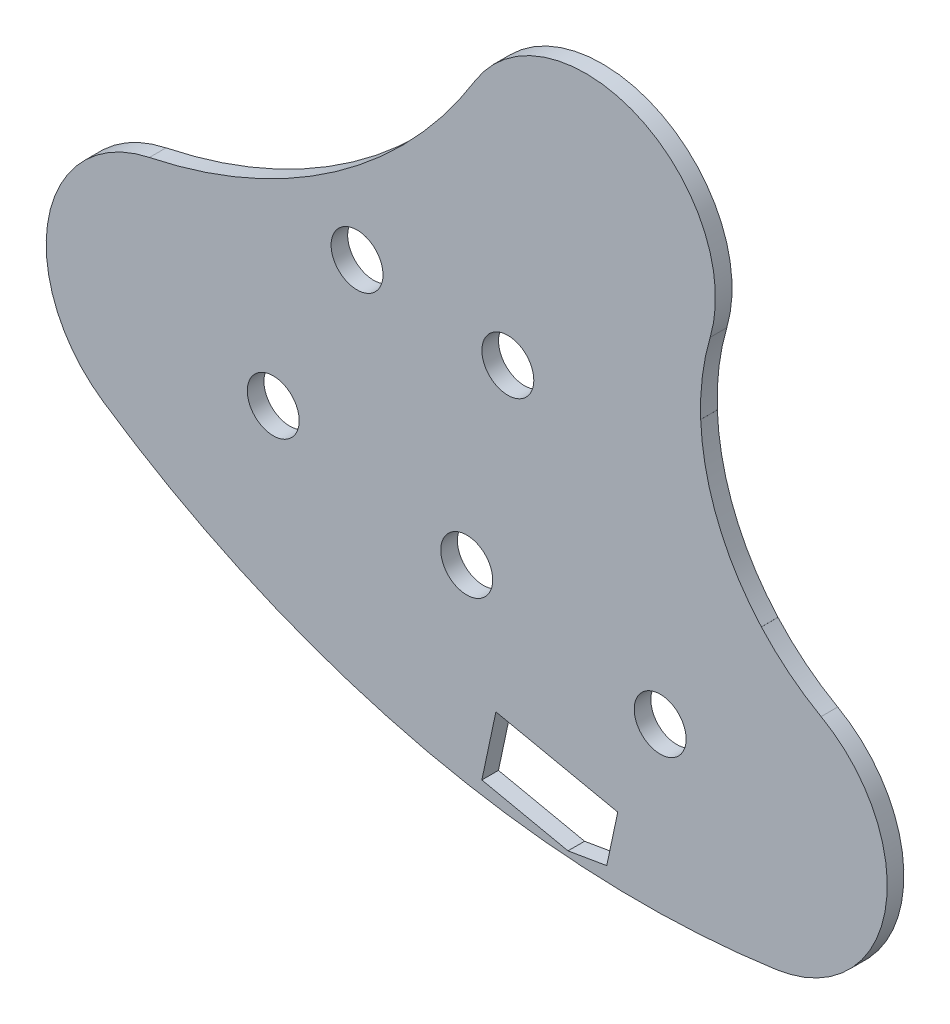
SolidWorks part; units mm, degrees
ref_plane "Front Plane" through (0, 0, 0) normal (0, 0, 1) x (1, 0, 0)
ref_plane "Top Plane" through (0, 0, 0) normal (0, 1, 0) x (1, 0, 0)
ref_plane "Right Plane" through (0, 0, 0) normal (1, 0, 0) x (0, 0, -1)
sketch "Sketch1" plane through (0, 0, 0) normal (0, 0, 1) x (1, 0, 0)
  line L0 (157.8919, 26.2701) -> (191.7747, 29.0915)
  line L1 (157.8919, 26.2701) -> (191.7747, 26.2701)
  line L2 (157.8919, 26.2701) -> (157.8919, 29.0915)
  line L3 (157.8919, 29.0915) -> (191.7747, 29.0915)
  line L4 (191.7747, 26.2701) -> (191.7747, 29.0915)
  line L5 (123.8919, 26.2701) -> (90.0092, 26.2701)
  line L6 (123.8919, 26.2701) -> (123.8919, 29.0915)
  line L7 (123.8919, 29.0915) -> (90.0092, 29.0915)
  line L8 (90.0092, 26.2701) -> (90.0092, 29.0915)
  line L9 (90.0092, 29.0915) -> (123.8919, 26.2701)
  line L10 (168.0919, 58.3601) -> (194.8735, 70.7292)
  line L11 (168.0919, 58.3601) -> (194.8735, 58.3601)
  line L12 (168.0919, 58.3601) -> (168.0919, 70.7292)
  line L13 (168.0919, 70.7292) -> (194.8735, 70.7292)
  line L14 (194.8735, 58.3601) -> (194.8735, 70.7292)
  line L15 (194.8735, 70.7292) -> (224.3587, 70.7292)
  line L16 (194.8735, 70.7292) -> (194.8735, 69.7923)
  line L17 (194.8735, 69.7923) -> (224.3587, 69.7923)
  line L18 (224.3587, 70.7292) -> (224.3587, 69.7923)
  line L19 (224.3587, 69.7923) -> (253.5106, 69.7923)
  line L20 (224.3587, 69.7923) -> (224.3587, 65.2742)
  line L21 (224.3587, 65.2742) -> (253.5106, 65.2742)
  line L22 (253.5106, 69.7923) -> (253.5106, 65.2742)
  line L23 (224.3587, 69.7923) -> (194.8735, 70.7292)
  line L24 (253.5106, 65.2742) -> (224.3587, 69.7923)
  line L25 (170.7502, 87.7401) -> (168.0919, 58.3601)
  line L26 (168.0919, 58.3601) -> (170.7502, 58.3601)
  line L27 (168.0919, 58.3601) -> (168.0919, 87.7401)
  line L28 (168.0919, 87.7401) -> (170.7502, 87.7401)
  line L29 (170.7502, 58.3601) -> (170.7502, 87.7401)
  line L30 (52.9966, 89.4705) -> (24.4119, 82.1791)
  line L31 (24.4119, 82.1791) -> (52.9966, 82.1791)
  line L32 (24.4119, 82.1791) -> (24.4119, 89.4705)
  line L33 (24.4119, 89.4705) -> (52.9966, 89.4705)
  line L34 (52.9966, 82.1791) -> (52.9966, 89.4705)
  line L35 (82.4966, 89.4705) -> (109.0019, 89.4705)
  line L36 (82.4966, 89.4705) -> (82.4966, 76.5201)
  line L37 (82.4966, 76.5201) -> (109.0019, 76.5201)
  line L38 (109.0019, 89.4705) -> (109.0019, 76.5201)
  line L39 (92.4554, 117.2387) -> (82.4966, 117.2387)
  line L40 (92.4554, 117.2387) -> (92.4554, 89.4705)
  line L41 (92.4554, 89.4705) -> (82.4966, 89.4705)
  line L42 (82.4966, 117.2387) -> (82.4966, 89.4705)
  line L43 (92.4554, 117.2387) -> (82.4966, 89.4705)
  line L44 (109.0019, 76.5201) -> (82.4966, 89.4705)
  circle A0 centre (123.8919, 26.2701) radius 14.25
  circle A1 centre (157.8919, 26.2701) radius 14.25
  circle A2 centre (90.0092, 29.0915) radius 14.25
  circle A3 centre (191.7747, 29.0915) radius 14.25
  circle A4 centre (82.4966, 89.4705) radius 11.25
  circle A5 centre (92.4554, 117.2387) radius 11.25
  circle A6 centre (52.9966, 89.4705) radius 11.25
  circle A7 centre (109.0019, 76.5201) radius 11.25
  circle A8 centre (24.4119, 82.1791) radius 11.25
  circle A9 centre (170.7502, 87.7401) radius 11.25
  circle A10 centre (168.0919, 58.3601) radius 11.25
  circle A11 centre (197.5318, 100.1092) radius 11.25
  circle A12 centre (194.8735, 70.7292) radius 11.25
  circle A13 centre (227.0169, 99.1723) radius 11.25
  circle A14 centre (224.3587, 69.7923) radius 11.25
  circle A15 centre (256.1689, 94.6541) radius 11.25
  circle A16 centre (253.5106, 65.2742) radius 11.25
  circle A17 centre (24.4119, 82.1791) radius 12
  circle A18 centre (52.9966, 89.4705) radius 12
  circle A19 centre (92.4554, 117.2387) radius 12
  circle A20 centre (82.4966, 89.4705) radius 12
  circle A21 centre (109.0019, 76.5201) radius 12
  circle A22 centre (168.0919, 58.3601) radius 12
  circle A23 centre (194.8735, 70.7292) radius 12
  circle A24 centre (224.3587, 69.7923) radius 12
  circle A25 centre (253.5106, 65.2742) radius 12
  circle A26 centre (256.1689, 94.6541) radius 12
  circle A27 centre (227.0169, 99.1723) radius 12
  circle A28 centre (197.5318, 100.1092) radius 12
  circle A29 centre (170.7502, 87.7401) radius 12
  circle A30 centre (191.7747, 29.0915) radius 15
  circle A31 centre (157.8919, 26.2701) radius 15
  circle A32 centre (123.8919, 26.2701) radius 15
  circle A33 centre (90.0092, 29.0915) radius 15
  circle A34 centre (173.429, 117.1182) radius 11.25
  circle A35 centre (173.429, 117.1182) radius 12
  dimension "D1" = 28.5
  dimension "D2" = 22.5
  dimension "D3" = 0.75
  dimension "D4" = 0.75
  dimension "D34" = 34
  dimension "D5" = 29.5
  dimension "D6" = 29.5
  dimension "D7" = 29.5
  dimension "D8" = 29.5
  dimension "D9" = 29.5
  dimension "D10" = 29.5
  dimension "D11" = 29.5
  dimension "D12" = 29.5
  dimension "D13" = 29.5
  dimension "D14" = 29.5
  dimension "D15" = 29.5
  dimension "D16" = 29.5
  dimension "D17" = 29.5
  dimension "D18" = 29.5
  dimension "D19" = 34
  dimension "D20" = 34
  dimension "D21" = 32.09
  dimension "D22" = 10.2
  dimension "D23" = 4.76
  dimension "D24" = 4.76
  dimension "D25" = 24.79
  dimension "D26" = 1.82
  dimension "D27" = 8.81
  dimension "D28" = 84.83
  dimension "D29" = 75.69
  dimension "D30" = 70.27
  dimension "D31" = 26.04
  dimension "D32" = 14.89
  dimension "D33" = 50.25
  dimension "D35" = 29.5
  dimension "D36" = 29.5
sketch "Sketch4" plane through (-30.2083, 20.075, 0) normal (0, 0, 1) x (0.9781, -0.2079, 0)
  line L0 (86.1706, 94.1917) -> (105.2206, 75.1417)
  line L1 (67.1206, 94.1917) -> (86.1706, 94.1917)
  line L2 (67.1206, 94.1917) -> (67.1206, 75.1417)
  line L3 (67.1206, 75.1417) -> (86.1706, 75.1417)
  line L4 (86.1706, 94.1917) -> (86.1706, 75.1417)
  line L5 (86.1706, 94.1917) -> (105.2206, 94.1917)
  line L6 (86.1706, 94.1917) -> (86.1706, 75.1417)
  line L7 (86.1706, 75.1417) -> (105.2206, 75.1417)
  line L8 (105.2206, 94.1917) -> (105.2206, 75.1417)
  line L9 (105.2206, 94.1917) -> (124.2706, 94.1917)
  line L10 (105.2206, 94.1917) -> (105.2206, 75.1417)
  line L11 (105.2206, 75.1417) -> (124.2706, 75.1417)
  line L12 (124.2706, 94.1917) -> (124.2706, 75.1417)
  line L13 (86.1706, 94.1917) -> (105.2206, 94.1917)
  line L14 (86.1706, 94.1917) -> (86.1706, 113.2417)
  line L15 (86.1706, 113.2417) -> (105.2206, 113.2417)
  line L16 (105.2206, 94.1917) -> (105.2206, 113.2417)
  line L17 (66.9585, 85.1784) -> (124.4326, 84.1551)
  point P14 (95.6956, 84.6667)
  point P15 (95.6956, 84.6667)
  dimension "D1" = 19.05
sketch "Sketch9" plane through (0, 0, 0) normal (0, 0, 1) x (1, 0, 0)
  line L1 (17.3619, 89.2291) -> (31.4619, 89.2291)
  line L2 (17.3619, 89.2291) -> (17.3619, 75.1291)
  line L3 (17.3619, 75.1291) -> (31.4619, 75.1291)
  line L4 (31.4619, 89.2291) -> (31.4619, 75.1291)
  line L5 (45.9466, 96.5205) -> (60.0466, 96.5205)
  line L6 (45.9466, 96.5205) -> (45.9466, 82.4205)
  line L7 (45.9466, 82.4205) -> (60.0466, 82.4205)
  line L8 (60.0466, 96.5205) -> (60.0466, 82.4205)
  line L9 (75.4466, 96.5205) -> (89.5466, 96.5205)
  line L10 (75.4466, 96.5205) -> (75.4466, 82.4205)
  line L11 (75.4466, 82.4205) -> (89.5466, 82.4205)
  line L12 (89.5466, 96.5205) -> (89.5466, 82.4205)
  line L13 (101.9519, 83.5701) -> (116.0519, 83.5701)
  line L14 (101.9519, 83.5701) -> (101.9519, 69.4701)
  line L15 (101.9519, 69.4701) -> (116.0519, 69.4701)
  line L16 (116.0519, 83.5701) -> (116.0519, 69.4701)
  line L17 (85.4054, 124.2887) -> (99.5054, 124.2887)
  line L18 (85.4054, 124.2887) -> (85.4054, 110.1887)
  line L19 (85.4054, 110.1887) -> (99.5054, 110.1887)
  line L20 (99.5054, 124.2887) -> (99.5054, 110.1887)
  line L21 (82.9592, 36.1415) -> (97.0592, 36.1415)
  line L22 (82.9592, 36.1415) -> (82.9592, 22.0415)
  line L23 (82.9592, 22.0415) -> (97.0592, 22.0415)
  line L24 (97.0592, 36.1415) -> (97.0592, 22.0415)
  line L25 (116.8419, 33.3201) -> (130.9419, 33.3201)
  line L26 (116.8419, 33.3201) -> (116.8419, 19.2201)
  line L27 (116.8419, 19.2201) -> (130.9419, 19.2201)
  line L28 (130.9419, 33.3201) -> (130.9419, 19.2201)
  line L29 (150.8419, 33.3201) -> (164.9419, 33.3201)
  line L30 (150.8419, 33.3201) -> (150.8419, 19.2201)
  line L31 (150.8419, 19.2201) -> (164.9419, 19.2201)
  line L32 (164.9419, 33.3201) -> (164.9419, 19.2201)
  line L33 (184.7247, 36.1415) -> (198.8247, 36.1415)
  line L34 (184.7247, 36.1415) -> (184.7247, 22.0415)
  line L35 (184.7247, 22.0415) -> (198.8247, 22.0415)
  line L36 (198.8247, 36.1415) -> (198.8247, 22.0415)
  line L37 (260.5606, 58.2242) -> (246.4606, 58.2242)
  line L38 (260.5606, 58.2242) -> (260.5606, 72.3242)
  line L39 (260.5606, 72.3242) -> (246.4606, 72.3242)
  line L40 (246.4606, 58.2242) -> (246.4606, 72.3242)
  line L41 (217.3087, 76.8423) -> (231.4087, 76.8423)
  line L42 (217.3087, 76.8423) -> (217.3087, 62.7423)
  line L43 (217.3087, 62.7423) -> (231.4087, 62.7423)
  line L44 (231.4087, 76.8423) -> (231.4087, 62.7423)
  line L45 (187.8235, 77.7792) -> (201.9235, 77.7792)
  line L46 (187.8235, 77.7792) -> (187.8235, 63.6792)
  line L47 (187.8235, 63.6792) -> (201.9235, 63.6792)
  line L48 (201.9235, 77.7792) -> (201.9235, 63.6792)
  line L49 (161.0419, 65.4101) -> (175.1419, 65.4101)
  line L50 (161.0419, 65.4101) -> (161.0419, 51.3101)
  line L51 (161.0419, 51.3101) -> (175.1419, 51.3101)
  line L52 (175.1419, 65.4101) -> (175.1419, 51.3101)
  line L53 (163.7002, 94.7901) -> (177.8002, 94.7901)
  line L54 (163.7002, 94.7901) -> (163.7002, 80.6901)
  line L55 (163.7002, 80.6901) -> (177.8002, 80.6901)
  line L56 (177.8002, 94.7901) -> (177.8002, 80.6901)
  line L57 (190.4818, 107.1592) -> (204.5818, 107.1592)
  line L58 (190.4818, 107.1592) -> (190.4818, 93.0592)
  line L59 (190.4818, 93.0592) -> (204.5818, 93.0592)
  line L60 (204.5818, 107.1592) -> (204.5818, 93.0592)
  line L61 (219.9669, 106.2223) -> (234.0669, 106.2223)
  line L62 (219.9669, 106.2223) -> (219.9669, 92.1223)
  line L63 (219.9669, 92.1223) -> (234.0669, 92.1223)
  line L64 (234.0669, 106.2223) -> (234.0669, 92.1223)
  line L65 (249.1189, 101.7041) -> (263.2189, 101.7041)
  line L66 (249.1189, 101.7041) -> (249.1189, 87.6041)
  line L67 (249.1189, 87.6041) -> (263.2189, 87.6041)
  line L68 (263.2189, 101.7041) -> (263.2189, 87.6041)
  line L69 (166.379, 124.1682) -> (180.479, 124.1682)
  line L70 (166.379, 124.1682) -> (166.379, 110.0682)
  line L71 (166.379, 110.0682) -> (180.479, 110.0682)
  line L72 (180.479, 124.1682) -> (180.479, 110.0682)
  point P72 (24.4119, 89.2291)
  point P74 (52.9966, 96.5205)
  point P76 (82.4966, 96.5205)
  point P78 (92.4554, 124.2887)
  point P80 (109.0019, 83.5701)
  point P82 (90.0092, 36.1415)
  point P84 (123.8919, 33.3201)
  point P86 (157.8919, 33.3201)
  point P88 (191.7747, 36.1415)
  point P90 (168.0919, 65.4101)
  point P92 (170.7502, 94.7901)
  point P94 (173.429, 124.1682)
  point P96 (197.5318, 107.1592)
  point P98 (227.0169, 106.2223)
  point P100 (256.1689, 101.7041)
  point P102 (194.8735, 77.7792)
  point P104 (224.3587, 76.8423)
  point P106 (253.5106, 72.3242)
  point P108 (17.3619, 82.1791)
  point P109 (45.9466, 89.4705)
  point P110 (75.4466, 89.4705)
  point P111 (101.9519, 76.5201)
  point P112 (85.4054, 117.2387)
  point P113 (82.9592, 29.0915)
  point P114 (116.8419, 26.2701)
  point P115 (150.8419, 26.2701)
  point P116 (184.7247, 29.0915)
  point P118 (161.0419, 58.3601)
  point P119 (187.8235, 70.7292)
  point P120 (217.3087, 69.7923)
  point P121 (246.4606, 65.2742)
  point P122 (163.7002, 87.7401)
  point P123 (190.4818, 100.1092)
  point P124 (219.9669, 99.1723)
  point P125 (249.1189, 94.6541)
  point P126 (166.379, 117.1182)
  dimension "D1" = 14.1
sketch "Sketch10" plane through (-22.0981, 19.3454, 0) normal (0, 0, 1) x (0.9781, -0.2079, 0)
  line L1 (61.5108, 90.7441) -> (75.6108, 90.7441)
  line L2 (61.5108, 90.7441) -> (61.5108, 76.6441)
  line L3 (61.5108, 76.6441) -> (75.6108, 76.6441)
  line L4 (75.6108, 90.7441) -> (75.6108, 76.6441)
  line L5 (80.5608, 90.7441) -> (94.6608, 90.7441)
  line L6 (80.5608, 90.7441) -> (80.5608, 76.6441)
  line L7 (80.5608, 76.6441) -> (94.6608, 76.6441)
  line L8 (94.6608, 90.7441) -> (94.6608, 76.6441)
  line L9 (99.6108, 90.7441) -> (113.7108, 90.7441)
  line L10 (99.6108, 90.7441) -> (99.6108, 76.6441)
  line L11 (99.6108, 76.6441) -> (113.7108, 76.6441)
  line L12 (113.7108, 90.7441) -> (113.7108, 76.6441)
  line L13 (80.5608, 109.7941) -> (94.6608, 109.7941)
  line L14 (80.5608, 109.7941) -> (80.5608, 95.6941)
  line L15 (80.5608, 95.6941) -> (94.6608, 95.6941)
  line L16 (94.6608, 109.7941) -> (94.6608, 95.6941)
  line L17 (50.5121, 89.6359) -> (53.4436, 75.8441) construction
  line L18 (59.0358, 93.2191) -> (78.0858, 93.2191) construction
  line L19 (78.0858, 112.2691) -> (97.1358, 112.2691) construction
  line L20 (97.1358, 93.2191) -> (116.1858, 93.2191) construction
  line L21 (78.0858, 93.2191) -> (78.0858, 112.2691) construction
  line L23 (59.0358, 93.2191) -> (59.0358, 74.1691) construction
  point P16 (75.6108, 83.6941)
  point P17 (94.6608, 83.6941)
  point P18 (113.7108, 83.6941)
  point P19 (87.6108, 90.7441)
  point P20 (87.6108, 109.7941)
  point P23 (68.5608, 90.7441)
  point P26 (68.5608, 93.2191)
  point P29 (87.6108, 112.2691)
  point P30 (106.6608, 90.7441)
  point P33 (106.6608, 93.2191)
  point P34 (80.5608, 102.7441)
  point P37 (78.0858, 102.7441)
  point P42 (59.0358, 83.6941)
  point P43 (61.5108, 83.6941)
sketch "Sketch14" plane through (0, 0, 0) normal (0, 0, 1) x (1, 0, 0)
  line L0 (165.1144, 80.6901) -> (163.7002, 82.1043)
  line L1 (163.7002, 93.3758) -> (165.1144, 94.7901)
  line L2 (177.8002, 93.3758) -> (176.386, 94.7901)
  line L3 (179.0648, 110.0682) -> (180.479, 111.4824)
  line L4 (166.379, 111.4824) -> (167.7932, 110.0682)
  line L5 (166.379, 122.754) -> (167.7932, 124.1682)
  line L6 (179.0648, 124.1682) -> (180.479, 122.754)
  line L7 (203.1676, 93.0592) -> (204.5818, 94.4734)
  line L8 (17.3619, 89.2291) -> (17.3619, 75.1291) construction
  line L9 (17.3619, 89.2291) -> (31.4619, 89.2291) construction
  line L10 (17.3619, 87.8149) -> (18.7761, 89.2291)
  line L11 (17.3619, 75.1291) -> (31.4619, 75.1291) construction
  line L12 (31.4619, 89.2291) -> (31.4619, 75.1291) construction
  line L13 (45.9466, 96.5205) -> (60.0466, 96.5205) construction
  line L14 (60.0466, 96.5205) -> (60.0466, 82.4205) construction
  line L15 (45.9466, 96.5205) -> (45.9466, 82.4205) construction
  line L16 (45.9466, 82.4205) -> (60.0466, 82.4205) construction
  line L17 (85.4054, 124.2887) -> (85.4054, 110.1887) construction
  line L18 (85.4054, 124.2887) -> (99.5054, 124.2887) construction
  line L19 (99.5054, 124.2887) -> (99.5054, 110.1887) construction
  line L20 (85.4054, 110.1887) -> (99.5054, 110.1887) construction
  line L21 (101.9519, 83.5701) -> (101.9519, 69.4701) construction
  line L22 (101.9519, 83.5701) -> (116.0519, 83.5701) construction
  line L23 (116.0519, 83.5701) -> (116.0519, 69.4701) construction
  line L24 (101.9519, 69.4701) -> (116.0519, 69.4701) construction
  line L25 (91.2712, 73.6044) -> (105.0631, 70.6729) construction
  line L26 (107.9947, 84.4647) -> (105.0631, 70.6729) construction
  line L27 (94.2028, 87.3963) -> (107.9947, 84.4647) construction
  line L28 (94.2028, 87.3963) -> (91.2712, 73.6044) construction
  line L29 (72.6375, 77.5651) -> (86.4294, 74.6336) construction
  line L30 (89.361, 88.4255) -> (86.4294, 74.6336) construction
  line L31 (75.5691, 91.357) -> (89.361, 88.4255) construction
  line L32 (75.5691, 91.357) -> (72.6375, 77.5651) construction
  line L33 (56.9354, 95.3177) -> (54.0038, 81.5259) construction
  line L34 (56.9354, 95.3177) -> (70.7273, 92.3862) construction
  line L35 (70.7273, 92.3862) -> (67.7957, 78.5943) construction
  line L36 (54.0038, 81.5259) -> (67.7957, 78.5943) construction
  line L37 (76.5983, 96.1988) -> (90.3901, 93.2673) construction
  line L38 (93.3217, 107.0592) -> (90.3901, 93.2673) construction
  line L39 (79.5298, 109.9907) -> (76.5983, 96.1988) construction
  line L40 (79.5298, 109.9907) -> (93.3217, 107.0592) construction
  line L41 (82.9592, 36.1415) -> (82.9592, 22.0415) construction
  line L42 (82.9592, 36.1415) -> (97.0592, 36.1415) construction
  line L43 (82.9592, 22.0415) -> (97.0592, 22.0415) construction
  line L44 (97.0592, 36.1415) -> (97.0592, 22.0415) construction
  line L45 (116.8419, 33.3201) -> (116.8419, 19.2201) construction
  line L46 (116.8419, 33.3201) -> (130.9419, 33.3201) construction
  line L47 (116.8419, 19.2201) -> (130.9419, 19.2201) construction
  line L48 (130.9419, 33.3201) -> (130.9419, 19.2201) construction
  line L49 (150.8419, 33.3201) -> (150.8419, 19.2201) construction
  line L50 (150.8419, 33.3201) -> (164.9419, 33.3201) construction
  line L51 (164.9419, 33.3201) -> (164.9419, 19.2201) construction
  line L52 (150.8419, 19.2201) -> (164.9419, 19.2201) construction
  line L53 (184.7247, 36.1415) -> (184.7247, 22.0415) construction
  line L54 (184.7247, 22.0415) -> (198.8247, 22.0415) construction
  line L55 (198.8247, 36.1415) -> (198.8247, 22.0415) construction
  line L56 (184.7247, 36.1415) -> (198.8247, 36.1415) construction
  line L57 (161.0419, 65.4101) -> (175.1419, 65.4101) construction
  line L58 (175.1419, 65.4101) -> (175.1419, 51.3101) construction
  line L59 (161.0419, 51.3101) -> (175.1419, 51.3101) construction
  line L60 (161.0419, 65.4101) -> (161.0419, 51.3101) construction
  line L61 (187.8235, 77.7792) -> (187.8235, 63.6792) construction
  line L62 (187.8235, 77.7792) -> (201.9235, 77.7792) construction
  line L63 (187.8235, 63.6792) -> (201.9235, 63.6792) construction
  line L64 (201.9235, 77.7792) -> (201.9235, 63.6792) construction
  line L65 (217.3087, 76.8423) -> (217.3087, 62.7423) construction
  line L66 (217.3087, 76.8423) -> (231.4087, 76.8423) construction
  line L67 (231.4087, 76.8423) -> (231.4087, 62.7423) construction
  line L68 (217.3087, 62.7423) -> (231.4087, 62.7423) construction
  line L69 (260.5606, 58.2242) -> (246.4606, 58.2242) construction
  line L70 (260.5606, 58.2242) -> (260.5606, 72.3242) construction
  line L71 (246.4606, 58.2242) -> (246.4606, 72.3242) construction
  line L72 (260.5606, 72.3242) -> (246.4606, 72.3242) construction
  line L73 (249.1189, 101.7041) -> (263.2189, 101.7041) construction
  line L74 (263.2189, 101.7041) -> (263.2189, 87.6041) construction
  line L75 (249.1189, 87.6041) -> (263.2189, 87.6041) construction
  line L76 (249.1189, 101.7041) -> (249.1189, 87.6041) construction
  line L77 (219.9669, 106.2223) -> (219.9669, 92.1223) construction
  line L78 (219.9669, 106.2223) -> (234.0669, 106.2223) construction
  line L79 (234.0669, 106.2223) -> (234.0669, 92.1223) construction
  line L80 (219.9669, 92.1223) -> (234.0669, 92.1223) construction
  line L81 (190.4818, 107.1592) -> (204.5818, 107.1592) construction
  line L82 (204.5818, 107.1592) -> (204.5818, 93.0592) construction
  line L83 (190.4818, 93.0592) -> (204.5818, 93.0592) construction
  line L84 (190.4818, 107.1592) -> (190.4818, 93.0592) construction
  line L85 (163.7002, 94.7901) -> (177.8002, 94.7901) construction
  line L86 (177.8002, 94.7901) -> (177.8002, 80.6901) construction
  line L87 (163.7002, 80.6901) -> (177.8002, 80.6901) construction
  line L88 (163.7002, 94.7901) -> (163.7002, 80.6901) construction
  line L89 (180.479, 124.1682) -> (180.479, 110.0682) construction
  line L90 (166.379, 110.0682) -> (180.479, 110.0682) construction
  line L91 (166.379, 124.1682) -> (166.379, 110.0682) construction
  line L92 (166.379, 124.1682) -> (180.479, 124.1682) construction
  line L93 (17.3619, 76.5433) -> (18.7761, 75.1291)
  line L94 (30.0477, 75.1291) -> (31.4619, 76.5433)
  line L95 (31.4619, 87.8149) -> (30.0477, 89.2291)
  line L96 (45.9466, 95.1063) -> (47.3608, 96.5205)
  line L97 (45.9466, 83.8347) -> (47.3608, 82.4205)
  line L98 (54.2979, 82.9092) -> (55.3871, 81.2318)
  line L99 (58.6323, 82.4205) -> (60.0466, 83.8347)
  line L100 (56.6413, 93.9344) -> (58.3187, 95.0237)
  line L101 (58.6323, 96.5205) -> (60.0466, 95.1063)
  line L102 (69.3439, 92.6802) -> (70.4332, 91.0029)
  line L103 (68.0897, 79.9776) -> (66.4124, 78.8883)
  line L104 (75.2751, 89.9737) -> (76.9524, 91.063)
  line L105 (72.9316, 78.9484) -> (74.0208, 77.2711)
  line L106 (85.0461, 74.9276) -> (86.7234, 76.0169)
  line L107 (89.0669, 87.0421) -> (87.9777, 88.7195)
  line L108 (89.0068, 93.5613) -> (90.6842, 94.6506)
  line L109 (76.8923, 97.5822) -> (77.9816, 95.9048)
  line L110 (91.9384, 107.3532) -> (93.0277, 105.6759)
  line L111 (79.2358, 108.6074) -> (80.9131, 109.6967)
  line L112 (85.4054, 111.6029) -> (86.8196, 110.1887)
  line L113 (98.0912, 110.1887) -> (99.5054, 111.6029)
  line L114 (98.0912, 124.2887) -> (99.5054, 122.8745)
  line L115 (85.4054, 122.8745) -> (86.8196, 124.2887)
  line L116 (93.9088, 86.013) -> (95.5861, 87.1023)
  line L117 (91.5653, 74.9877) -> (92.6546, 73.3104)
  line L118 (103.6798, 70.9669) -> (105.3572, 72.0562)
  line L119 (106.6114, 84.7588) -> (107.7006, 83.0814)
  line L120 (101.9519, 82.1559) -> (103.3662, 83.5701)
  line L121 (101.9519, 70.8843) -> (103.3662, 69.4701)
  line L122 (114.6377, 69.4701) -> (116.0519, 70.8843)
  line L123 (116.0519, 82.1559) -> (114.6377, 83.5701)
  line L124 (82.9592, 34.7272) -> (84.3734, 36.1415)
  line L125 (82.9592, 23.4557) -> (84.3734, 22.0415)
  line L126 (95.645, 22.0415) -> (97.0592, 23.4557)
  line L127 (97.0592, 34.7272) -> (95.645, 36.1415)
  line L128 (116.8419, 31.9059) -> (118.2562, 33.3201)
  line L129 (116.8419, 20.6343) -> (118.2562, 19.2201)
  line L130 (129.5277, 19.2201) -> (130.9419, 20.6343)
  line L131 (130.9419, 31.9059) -> (129.5277, 33.3201)
  line L132 (150.8419, 31.9059) -> (152.2562, 33.3201)
  line L133 (150.8419, 20.6343) -> (152.2562, 19.2201)
  line L134 (163.5277, 19.2201) -> (164.9419, 20.6343)
  line L135 (164.9419, 31.9059) -> (163.5277, 33.3201)
  line L136 (184.7247, 34.7272) -> (186.1389, 36.1415)
  line L137 (184.7247, 23.4557) -> (186.1389, 22.0415)
  line L138 (197.4105, 22.0415) -> (198.8247, 23.4557)
  line L139 (198.8247, 34.7272) -> (197.4105, 36.1415)
  line L140 (173.7277, 51.3101) -> (175.1419, 52.7243)
  line L141 (161.0419, 52.7243) -> (162.4562, 51.3101)
  line L142 (161.0419, 63.9959) -> (162.4562, 65.4101)
  line L143 (173.7277, 65.4101) -> (175.1419, 63.9959)
  line L144 (187.8235, 65.0934) -> (189.2378, 63.6792)
  line L145 (200.5093, 63.6792) -> (201.9235, 65.0934)
  line L146 (200.5093, 77.7792) -> (201.9235, 76.365)
  line L147 (187.8235, 76.365) -> (189.2378, 77.7792)
  line L148 (176.386, 80.6901) -> (177.8002, 82.1043)
  line L149 (204.5818, 105.745) -> (203.1676, 107.1592)
  line L150 (191.896, 107.1592) -> (190.4818, 105.745)
  line L151 (190.4818, 94.4734) -> (191.896, 93.0592)
  line L152 (219.9669, 104.8081) -> (221.3812, 106.2223)
  line L153 (232.6527, 106.2223) -> (234.0669, 104.8081)
  line L154 (234.0669, 93.5365) -> (232.6527, 92.1223)
  line L155 (219.9669, 93.5365) -> (221.3812, 92.1223)
  line L156 (229.9944, 76.8423) -> (231.4087, 75.4281)
  line L157 (217.3087, 75.4281) -> (218.7229, 76.8423)
  line L158 (217.3087, 64.1565) -> (218.7229, 62.7423)
  line L159 (229.9944, 62.7423) -> (231.4087, 64.1565)
  line L160 (259.1464, 72.3242) -> (260.5606, 70.9099)
  line L161 (246.4606, 70.9099) -> (247.8748, 72.3242)
  line L162 (259.1464, 58.2242) -> (260.5606, 59.6384)
  line L163 (247.8748, 58.2242) -> (246.4606, 59.6384)
  line L164 (261.8047, 87.6041) -> (263.2189, 89.0183)
  line L165 (249.1189, 89.0183) -> (250.5331, 87.6041)
  line L166 (249.1189, 100.2899) -> (250.5331, 101.7041)
  line L167 (261.8047, 101.7041) -> (263.2189, 100.2899)
  line L168 (75.4466, 96.5205) -> (75.4466, 82.4205) construction
  line L169 (75.4466, 96.5205) -> (89.5466, 96.5205) construction
  line L170 (89.5466, 96.5205) -> (89.5466, 82.4205) construction
  line L171 (75.4466, 82.4205) -> (89.5466, 82.4205) construction
  line L172 (76.8608, 96.5205) -> (75.4466, 95.1063)
  line L173 (88.1323, 96.5205) -> (89.5466, 95.1063)
  line L174 (89.5466, 83.8347) -> (88.1323, 82.4205)
  line L175 (75.4466, 83.8347) -> (76.8608, 82.4205)
  arc A0 (17.3619, 87.8149) -> (18.7761, 89.2291) centre (18.069, 88.522) cw
  arc A1 (18.7761, 75.1291) -> (17.3619, 76.5433) centre (18.069, 75.8362) cw
  arc A2 (31.4619, 76.5433) -> (30.0477, 75.1291) centre (30.7548, 75.8362) cw
  arc A3 (30.0477, 89.2291) -> (31.4619, 87.8149) centre (30.7548, 88.522) cw
  arc A4 (58.6323, 96.5205) -> (60.0466, 95.1063) centre (59.3394, 95.8134) cw
  arc A5 (45.9466, 95.1063) -> (47.3608, 96.5205) centre (46.6537, 95.8134) cw
  arc A6 (47.3608, 82.4205) -> (45.9466, 83.8347) centre (46.6537, 83.1276) cw
  arc A7 (60.0466, 83.8347) -> (58.6323, 82.4205) centre (59.3394, 83.1276) cw
  arc A8 (85.4054, 122.8745) -> (86.8196, 124.2887) centre (86.1125, 123.5816) cw
  arc A9 (98.0912, 124.2887) -> (99.5054, 122.8745) centre (98.7983, 123.5816) cw
  arc A10 (99.5054, 111.6029) -> (98.0912, 110.1887) centre (98.7983, 110.8958) cw
  arc A11 (85.4054, 111.6029) -> (86.8196, 110.1887) centre (86.1125, 110.8958) ccw
  arc A12 (101.9519, 82.1559) -> (103.3662, 83.5701) centre (102.6591, 82.863) cw
  arc A13 (114.6377, 83.5701) -> (116.0519, 82.1559) centre (115.3448, 82.863) cw
  arc A14 (116.0519, 70.8843) -> (114.6377, 69.4701) centre (115.3448, 70.1772) cw
  arc A15 (101.9519, 70.8843) -> (103.3662, 69.4701) centre (102.6591, 70.1772) ccw
  arc A16 (103.6798, 70.9669) -> (105.3572, 72.0562) centre (104.5185, 71.5115) ccw
  arc A17 (106.6114, 84.7588) -> (107.7006, 83.0814) centre (107.156, 83.9201) cw
  arc A18 (93.9088, 86.013) -> (95.5861, 87.1023) centre (94.7474, 86.5576) cw
  arc A19 (91.5653, 74.9877) -> (92.6546, 73.3104) centre (92.1099, 74.1491) ccw
  arc A20 (85.0461, 74.9276) -> (86.7234, 76.0169) centre (85.8848, 75.4722) ccw
  arc A21 (87.9777, 88.7195) -> (89.0669, 87.0421) centre (88.5223, 87.8808) cw
  arc A22 (75.2751, 89.9737) -> (76.9524, 91.063) centre (76.1137, 90.5183) cw
  arc A23 (72.9316, 78.9484) -> (74.0208, 77.2711) centre (73.4762, 78.1098) ccw
  arc A24 (56.6413, 93.9344) -> (58.3187, 95.0237) centre (57.48, 94.4791) cw
  arc A25 (69.3439, 92.6802) -> (70.4332, 91.0029) centre (69.8886, 91.8415) cw
  arc A26 (68.0897, 79.9776) -> (66.4124, 78.8883) centre (67.2511, 79.433) cw
  arc A27 (54.2979, 82.9092) -> (55.3871, 81.2318) centre (54.8425, 82.0705) ccw
  arc A28 (89.0068, 93.5613) -> (90.6842, 94.6506) centre (89.8455, 94.106) ccw
  arc A29 (76.8923, 97.5822) -> (77.9816, 95.9048) centre (77.4369, 96.7435) ccw
  arc A30 (79.2358, 108.6074) -> (80.9131, 109.6967) centre (80.0744, 109.1521) cw
  arc A31 (91.9384, 107.3532) -> (93.0277, 105.6759) centre (92.483, 106.5145) cw
  arc A32 (82.9592, 34.7272) -> (84.3734, 36.1415) centre (83.6663, 35.4344) cw
  arc A33 (82.9592, 23.4557) -> (84.3734, 22.0415) centre (83.6663, 22.7486) ccw
  arc A34 (95.645, 22.0415) -> (97.0592, 23.4557) centre (96.3521, 22.7486) ccw
  arc A35 (95.645, 36.1415) -> (97.0592, 34.7272) centre (96.3521, 35.4344) cw
  arc A36 (116.8419, 31.9059) -> (118.2562, 33.3201) centre (117.5491, 32.613) cw
  arc A37 (116.8419, 20.6343) -> (118.2562, 19.2201) centre (117.5491, 19.9272) ccw
  arc A38 (129.5277, 19.2201) -> (130.9419, 20.6343) centre (130.2348, 19.9272) ccw
  arc A39 (129.5277, 33.3201) -> (130.9419, 31.9059) centre (130.2348, 32.613) cw
  arc A40 (150.8419, 31.9059) -> (152.2562, 33.3201) centre (151.5491, 32.613) cw
  arc A41 (163.5277, 33.3201) -> (164.9419, 31.9059) centre (164.2348, 32.613) cw
  arc A42 (164.9419, 20.6343) -> (163.5277, 19.2201) centre (164.2348, 19.9272) cw
  arc A43 (150.8419, 20.6343) -> (152.2562, 19.2201) centre (151.5491, 19.9272) ccw
  arc A44 (184.7247, 23.4557) -> (186.1389, 22.0415) centre (185.4318, 22.7486) ccw
  arc A45 (197.4105, 22.0415) -> (198.8247, 23.4557) centre (198.1176, 22.7486) ccw
  arc A46 (197.4105, 36.1415) -> (198.8247, 34.7272) centre (198.1176, 35.4344) cw
  arc A47 (184.7247, 34.7272) -> (186.1389, 36.1415) centre (185.4318, 35.4344) cw
  arc A48 (173.7277, 65.4101) -> (175.1419, 63.9959) centre (174.4348, 64.703) cw
  arc A49 (175.1419, 52.7243) -> (173.7277, 51.3101) centre (174.4348, 52.0172) cw
  arc A50 (161.0419, 52.7243) -> (162.4562, 51.3101) centre (161.7491, 52.0172) ccw
  arc A51 (161.0419, 63.9959) -> (162.4562, 65.4101) centre (161.7491, 64.703) cw
  arc A52 (187.8235, 76.365) -> (189.2378, 77.7792) centre (188.5306, 77.0721) cw
  arc A53 (187.8235, 65.0934) -> (189.2378, 63.6792) centre (188.5306, 64.3863) ccw
  arc A54 (200.5093, 63.6792) -> (201.9235, 65.0934) centre (201.2164, 64.3863) ccw
  arc A55 (200.5093, 77.7792) -> (201.9235, 76.365) centre (201.2164, 77.0721) cw
  arc A56 (217.3087, 75.4281) -> (218.7229, 76.8423) centre (218.0158, 76.1352) cw
  arc A57 (229.9944, 76.8423) -> (231.4087, 75.4281) centre (230.7016, 76.1352) cw
  arc A58 (231.4087, 64.1565) -> (229.9944, 62.7423) centre (230.7016, 63.4494) cw
  arc A59 (217.3087, 64.1565) -> (218.7229, 62.7423) centre (218.0158, 63.4494) ccw
  arc A60 (259.1464, 58.2242) -> (260.5606, 59.6384) centre (259.8535, 58.9313) ccw
  arc A61 (246.4606, 59.6384) -> (247.8748, 58.2242) centre (247.1677, 58.9313) ccw
  arc A62 (246.4606, 70.9099) -> (247.8748, 72.3242) centre (247.1677, 71.617) cw
  arc A63 (259.1464, 72.3242) -> (260.5606, 70.9099) centre (259.8535, 71.617) cw
  arc A64 (261.8047, 101.7041) -> (263.2189, 100.2899) centre (262.5118, 100.997) cw
  arc A65 (263.2189, 89.0183) -> (261.8047, 87.6041) centre (262.5118, 88.3112) cw
  arc A66 (250.5331, 87.6041) -> (249.1189, 89.0183) centre (249.826, 88.3112) cw
  arc A67 (249.1189, 100.2899) -> (250.5331, 101.7041) centre (249.826, 100.997) cw
  arc A68 (219.9669, 104.8081) -> (221.3812, 106.2223) centre (220.674, 105.5152) cw
  arc A69 (232.6527, 106.2223) -> (234.0669, 104.8081) centre (233.3598, 105.5152) cw
  arc A70 (234.0669, 93.5365) -> (232.6527, 92.1223) centre (233.3598, 92.8294) cw
  arc A71 (221.3812, 92.1223) -> (219.9669, 93.5365) centre (220.674, 92.8294) cw
  arc A72 (203.1676, 107.1592) -> (204.5818, 105.745) centre (203.8747, 106.4521) cw
  arc A73 (204.5818, 94.4734) -> (203.1676, 93.0592) centre (203.8747, 93.7663) cw
  arc A74 (191.896, 93.0592) -> (190.4818, 94.4734) centre (191.1889, 93.7663) cw
  arc A75 (190.4818, 105.745) -> (191.896, 107.1592) centre (191.1889, 106.4521) cw
  arc A76 (176.386, 94.7901) -> (177.8002, 93.3758) centre (177.0931, 94.0829) cw
  arc A77 (177.8002, 82.1043) -> (176.386, 80.6901) centre (177.0931, 81.3972) cw
  arc A78 (165.1144, 80.6901) -> (163.7002, 82.1043) centre (164.4073, 81.3972) cw
  arc A79 (163.7002, 93.3758) -> (165.1144, 94.7901) centre (164.4073, 94.0829) cw
  arc A80 (180.479, 111.4824) -> (179.0648, 110.0682) centre (179.7719, 110.7753) cw
  arc A81 (167.7932, 110.0682) -> (166.379, 111.4824) centre (167.0861, 110.7753) cw
  arc A82 (179.0648, 124.1682) -> (180.479, 122.754) centre (179.7719, 123.4611) cw
  arc A83 (166.379, 122.754) -> (167.7932, 124.1682) centre (167.0861, 123.4611) cw
  arc A84 (75.4466, 95.1063) -> (76.8608, 96.5205) centre (76.1537, 95.8134) cw
  arc A85 (88.1323, 96.5205) -> (89.5466, 95.1063) centre (88.8394, 95.8134) cw
  arc A86 (89.5466, 83.8347) -> (88.1323, 82.4205) centre (88.8394, 83.1276) cw
  arc A87 (76.8608, 82.4205) -> (75.4466, 83.8347) centre (76.1537, 83.1276) cw
  dimension "D1" = 45
  dimension "D2" = 1
  dimension "D71" = 45
  dimension "D3" = 45
  dimension "D4" = 45
  dimension "D5" = 45
  dimension "D6" = 45
  dimension "D7" = 45
  dimension "D8" = 45
  dimension "D9" = 45
  dimension "D10" = 45
  dimension "D11" = 45
  dimension "D12" = 45
  dimension "D13" = 45
  dimension "D14" = 45
  dimension "D15" = 45
  dimension "D16" = 45
  dimension "D17" = 45
  dimension "D18" = 45
  dimension "D19" = 45
  dimension "D20" = 45
  dimension "D21" = 45
  dimension "D22" = 45
  dimension "D23" = 45
  dimension "D24" = 45
  dimension "D25" = 45
  dimension "D26" = 45
  dimension "D27" = 45
  dimension "D28" = 45
  dimension "D29" = 45
  dimension "D30" = 45
  dimension "D31" = 45
  dimension "D32" = 45
  dimension "D33" = 45
  dimension "D34" = 45
  dimension "D35" = 45
  dimension "D36" = 45
  dimension "D37" = 45
  dimension "D38" = 45
  dimension "D39" = 45
  dimension "D40" = 45
  dimension "D41" = 45
  dimension "D42" = 45
  dimension "D43" = 45
  dimension "D44" = 45
  dimension "D45" = 45
  dimension "D46" = 45
  dimension "D47" = 45
  dimension "D48" = 45
  dimension "D49" = 45
  dimension "D50" = 45
  dimension "D51" = 45
  dimension "D52" = 45
  dimension "D53" = 45
  dimension "D54" = 45
  dimension "D55" = 45
  dimension "D56" = 45
  dimension "D57" = 45
  dimension "D58" = 45
  dimension "D59" = 45
  dimension "D60" = 45
  dimension "D61" = 45
  dimension "D62" = 45
  dimension "D63" = 45
  dimension "D64" = 45
  dimension "D65" = 45
  dimension "D66" = 45
  dimension "D67" = 45
  dimension "D68" = 45
  dimension "D69" = 45
  dimension "D70" = 45
  dimension "D72" = 45
  dimension "D73" = 45
  dimension "D74" = 45
  dimension "D75" = 45
  dimension "D76" = 45
  dimension "D77" = 45
  dimension "D78" = 45
  dimension "D79" = 45
  dimension "D80" = 45
  dimension "D81" = 45
  dimension "D82" = 45
  dimension "D83" = 45
  dimension "D84" = 45
  dimension "D85" = 45
  dimension "D86" = 45
  dimension "D87" = 45
  dimension "D88" = 45
  dimension "D89" = 45
sketch "Sketch16" plane through (0, 0, 0) normal (0, 0, 1) x (1, 0, 0)
  line L0 (81.0092, 30.6915) -> (99.0092, 30.6915)
  line L5 (17.3619, 89.2291) -> (17.3619, 75.1291) construction
  line L6 (81.0092, 30.6915) -> (81.0092, 27.4915)
  line L7 (17.3619, 75.1291) -> (31.4619, 75.1291) construction
  line L8 (15.4119, 83.7791) -> (33.4119, 83.7791)
  line L9 (15.4119, 83.7791) -> (15.4119, 80.5791)
  line L10 (15.4119, 80.5791) -> (33.4119, 80.5791)
  line L11 (33.4119, 83.7791) -> (33.4119, 80.5791)
  line L12 (81.0092, 27.4915) -> (99.0092, 27.4915)
  line L13 (99.0092, 30.6915) -> (99.0092, 27.4915)
  line L14 (114.8919, 27.8701) -> (132.8919, 27.8701)
  line L15 (114.8919, 27.8701) -> (114.8919, 24.6701)
  line L16 (114.8919, 24.6701) -> (132.8919, 24.6701)
  line L17 (132.8919, 27.8701) -> (132.8919, 24.6701)
  line L18 (148.8919, 27.8701) -> (166.8919, 27.8701)
  line L19 (148.8919, 27.8701) -> (148.8919, 24.6701)
  line L20 (148.8919, 24.6701) -> (166.8919, 24.6701)
  line L21 (166.8919, 27.8701) -> (166.8919, 24.6701)
  line L22 (182.7747, 30.6915) -> (200.7747, 30.6915)
  line L23 (182.7747, 30.6915) -> (182.7747, 27.4915)
  line L24 (182.7747, 27.4915) -> (200.7747, 27.4915)
  line L25 (200.7747, 30.6915) -> (200.7747, 27.4915)
  line L26 (43.9966, 91.0705) -> (61.9966, 91.0705)
  line L27 (43.9966, 91.0705) -> (43.9966, 87.8705)
  line L28 (43.9966, 87.8705) -> (61.9966, 87.8705)
  line L29 (61.9966, 91.0705) -> (61.9966, 87.8705)
  line L30 (73.4966, 91.0705) -> (91.4966, 91.0705)
  line L31 (73.4966, 91.0705) -> (73.4966, 87.8705)
  line L32 (73.4966, 87.8705) -> (91.4966, 87.8705)
  line L33 (91.4966, 91.0705) -> (91.4966, 87.8705)
  line L34 (100.0019, 78.1201) -> (118.0019, 78.1201)
  line L35 (100.0019, 78.1201) -> (100.0019, 74.9201)
  line L36 (100.0019, 74.9201) -> (118.0019, 74.9201)
  line L37 (118.0019, 78.1201) -> (118.0019, 74.9201)
  line L38 (83.4554, 118.8387) -> (101.4554, 118.8387)
  line L39 (83.4554, 118.8387) -> (83.4554, 115.6387)
  line L40 (83.4554, 115.6387) -> (101.4554, 115.6387)
  line L41 (101.4554, 118.8387) -> (101.4554, 115.6387)
  line L42 (164.429, 118.7182) -> (182.429, 118.7182)
  line L43 (164.429, 118.7182) -> (164.429, 115.5182)
  line L44 (164.429, 115.5182) -> (182.429, 115.5182)
  line L45 (182.429, 118.7182) -> (182.429, 115.5182)
  line L46 (161.7502, 89.3401) -> (179.7502, 89.3401)
  line L47 (161.7502, 89.3401) -> (161.7502, 86.1401)
  line L48 (161.7502, 86.1401) -> (179.7502, 86.1401)
  line L49 (179.7502, 89.3401) -> (179.7502, 86.1401)
  line L50 (188.5318, 101.7092) -> (206.5318, 101.7092)
  line L51 (188.5318, 101.7092) -> (188.5318, 98.5092)
  line L52 (188.5318, 98.5092) -> (206.5318, 98.5092)
  line L53 (206.5318, 101.7092) -> (206.5318, 98.5092)
  line L54 (159.0919, 59.9601) -> (177.0919, 59.9601)
  line L55 (159.0919, 59.9601) -> (159.0919, 56.7601)
  line L56 (159.0919, 56.7601) -> (177.0919, 56.7601)
  line L57 (177.0919, 59.9601) -> (177.0919, 56.7601)
  line L58 (185.8735, 72.3292) -> (203.8735, 72.3292)
  line L59 (185.8735, 72.3292) -> (185.8735, 69.1292)
  line L60 (185.8735, 69.1292) -> (203.8735, 69.1292)
  line L61 (203.8735, 72.3292) -> (203.8735, 69.1292)
  line L62 (218.0169, 100.7723) -> (236.0169, 100.7723)
  line L63 (218.0169, 100.7723) -> (218.0169, 97.5723)
  line L64 (218.0169, 97.5723) -> (236.0169, 97.5723)
  line L65 (236.0169, 100.7723) -> (236.0169, 97.5723)
  line L66 (215.3587, 71.3923) -> (233.3587, 71.3923)
  line L67 (215.3587, 71.3923) -> (215.3587, 68.1923)
  line L68 (215.3587, 68.1923) -> (233.3587, 68.1923)
  line L69 (233.3587, 71.3923) -> (233.3587, 68.1923)
  line L70 (247.1689, 96.2541) -> (265.1689, 96.2541)
  line L71 (247.1689, 96.2541) -> (247.1689, 93.0541)
  line L72 (247.1689, 93.0541) -> (265.1689, 93.0541)
  line L73 (265.1689, 96.2541) -> (265.1689, 93.0541)
  line L74 (244.5106, 66.8742) -> (262.5106, 66.8742)
  line L75 (244.5106, 66.8742) -> (244.5106, 63.6742)
  line L76 (244.5106, 63.6742) -> (262.5106, 63.6742)
  line L77 (262.5106, 66.8742) -> (262.5106, 63.6742)
  circle A0 centre (15.4119, 82.1791) radius 1.6
  circle A1 centre (33.4119, 82.1791) radius 1.6
  circle A2 centre (81.0092, 29.0915) radius 1.6
  circle A3 centre (99.0092, 29.0915) radius 1.6
  circle A4 centre (114.8919, 26.2701) radius 1.6
  circle A5 centre (132.8919, 26.2701) radius 1.6
  circle A6 centre (148.8919, 26.2701) radius 1.6
  circle A7 centre (166.8919, 26.2701) radius 1.6
  circle A8 centre (182.7747, 29.0915) radius 1.6
  circle A9 centre (200.7747, 29.0915) radius 1.6
  circle A10 centre (43.9966, 89.4705) radius 1.6
  circle A11 centre (61.9966, 89.4705) radius 1.6
  circle A12 centre (73.4966, 89.4705) radius 1.6
  circle A13 centre (91.4966, 89.4705) radius 1.6
  circle A14 centre (100.0019, 76.5201) radius 1.6
  circle A15 centre (118.0019, 76.5201) radius 1.6
  circle A16 centre (83.4554, 117.2387) radius 1.6
  circle A17 centre (101.4554, 117.2387) radius 1.6
  circle A18 centre (164.429, 117.1182) radius 1.6
  circle A19 centre (182.429, 117.1182) radius 1.6
  circle A20 centre (161.7502, 87.7401) radius 1.6
  circle A21 centre (179.7502, 87.7401) radius 1.6
  circle A22 centre (188.5318, 100.1092) radius 1.6
  circle A23 centre (206.5318, 100.1092) radius 1.6
  circle A24 centre (159.0919, 58.3601) radius 1.6
  circle A25 centre (177.0919, 58.3601) radius 1.6
  circle A26 centre (185.8735, 70.7292) radius 1.6
  circle A27 centre (203.8735, 70.7292) radius 1.6
  circle A28 centre (218.0169, 99.1723) radius 1.6
  circle A29 centre (236.0169, 99.1723) radius 1.6
  circle A30 centre (215.3587, 69.7923) radius 1.6
  circle A31 centre (233.3587, 69.7923) radius 1.6
  circle A32 centre (247.1689, 94.6541) radius 1.6
  circle A33 centre (265.1689, 94.6541) radius 1.6
  circle A34 centre (244.5106, 65.2742) radius 1.6
  circle A35 centre (262.5106, 65.2742) radius 1.6
  point P2 (24.4119, 75.1291)
  point P6 (17.3619, 82.1791)
  point P14 (24.4119, 80.5791)
  point P53 (90.0092, 30.6915)
  point P57 (123.8919, 27.8701)
  point P60 (157.8919, 27.8701)
  point P63 (191.7747, 30.6915)
  point P73 (52.9966, 91.0705)
  point P83 (82.4966, 91.0705)
  point P93 (109.0019, 78.1201)
  point P103 (92.4554, 118.8387)
  point P113 (173.429, 118.7182)
  point P123 (170.7502, 89.3401)
  point P133 (197.5318, 101.7092)
  point P143 (168.0919, 59.9601)
  point P153 (194.8735, 72.3292)
  point P163 (227.0169, 100.7723)
  point P173 (224.3587, 71.3923)
  point P183 (256.1689, 96.2541)
  point P193 (253.5106, 66.8742)
  dimension "D1" = 3.2
  dimension "D2" = 18
sketch "Sketch8" plane through (0, 0, 0) normal (0, 0, 1) x (1, 0, 0)
  line L0 (52.2844, 74.6389) -> (82.4966, 89.4705)
  line L1 (86.9403, 110.9459) -> (79.0189, 73.6784)
  line L2 (77.6235, 112.9262) -> (96.2572, 108.9655) construction
  line L3 (69.702, 75.6588) -> (88.3357, 71.6981) construction
  line L4 (53.3861, 72.3947) -> (55.5425, 73.4534)
  line L5 (99.6829, 63.2465) -> (101.1557, 61.3487)
  line L6 (103.1308, 62.8814) -> (82.4966, 89.4705)
  line L8 (73.6628, 94.2925) -> (77.6235, 112.9262) construction
  line L9 (55.029, 98.2532) -> (73.6628, 94.2925) construction
  line L13 (93.9017, 130.158) -> (94.0202, 130.4883)
  line L14 (99.5495, 128.1325) -> (99.6679, 128.4628)
  line L16 (99.4417, 62.7418) -> (100.7607, 61.0421)
  line L17 (55.5377, 72.894) -> (53.6064, 71.9459)
  line L19 (82.4966, 89.4705) -> (96.8441, 129.4755)
  circle A1 centre (57.4203, 106.4022) radius 2.5
  circle A2 centre (106.0456, 106.2134) radius 2.5
  circle A3 centre (76.7673, 63.0854) radius 2.5
  circle A4 centre (52.9966, 89.4705) radius 13
  circle A6 centre (92.4554, 117.2387) radius 13
  circle A7 centre (109.0019, 76.5201) radius 13
  circle A8 centre (82.4966, 89.4705) radius 25
  arc A10 (50.3337, 102.1949) -> (81.377, 124.0408) centre (40.5107, 149.1329) ccw
  circle A11 centre (103.1308, 62.8814) radius 2.5
  circle A12 centre (52.2844, 74.6389) radius 2.5
  circle A13 centre (96.8441, 129.4755) radius 2.5
  circle A14 centre (52.2844, 74.6389) radius 3
  circle A15 centre (103.1308, 62.8814) radius 3
  circle A16 centre (96.8441, 129.4755) radius 3
  arc A17 (104.9258, 113.5659) -> (115.3756, 87.8504) centre (126.3001, 107.2707) ccw
  arc A18 (45.7038, 78.7088) -> (110.8301, 63.6492) centre (97.7768, 155.5511) ccw
  circle A19 centre (92.4554, 117.2387) radius 15
  circle A20 centre (109.0019, 76.5201) radius 15
  circle A21 centre (52.9966, 89.4705) radius 15
  circle A22 centre (82.4966, 89.4705) radius 27
  arc A23 (44.5818, 77.0531) -> (111.1113, 61.6691) centre (97.7768, 155.5511) ccw
  arc A24 (49.924, 104.1525) -> (79.6727, 125.0873) centre (40.5107, 149.1329) ccw
  arc A25 (106.8443, 113.0008) -> (116.3562, 89.5935) centre (126.3001, 107.2707) ccw
  circle A26 centre (52.9966, 89.4705) radius 12.5
  circle A27 centre (109.0019, 76.5201) radius 12.5
  circle A28 centre (92.4554, 117.2387) radius 12.5
  circle A29 centre (82.4966, 89.4705) radius 24.5
  arc A30 (104.4462, 113.7071) -> (115.1305, 87.4146) centre (126.3001, 107.2707) ccw
  arc A31 (110.7597, 64.1443) -> (45.9842, 79.1227) centre (97.7768, 155.5511) cw
  arc A32 (50.4361, 101.7055) -> (81.8031, 123.7792) centre (40.5107, 149.1329) ccw
  circle A33 centre (52.9966, 89.4705) radius 15.5
  circle A34 centre (109.0019, 76.5201) radius 15.5
  circle A35 centre (92.4554, 117.2387) radius 15.5
  circle A36 centre (82.4966, 89.4705) radius 27.5
  arc A37 (107.3239, 112.8596) -> (116.6013, 90.0293) centre (126.3001, 107.2707) ccw
  arc A38 (111.1816, 61.1741) -> (44.3013, 76.6392) centre (97.7768, 155.5511) cw
  arc A39 (49.8216, 104.6419) -> (79.2466, 125.349) centre (40.5107, 149.1329) ccw
  circle A40 centre (106.0456, 106.2134) radius 3
  circle A41 centre (76.7673, 63.0854) radius 3
  circle A42 centre (57.4203, 106.4022) radius 3
  circle A43 centre (70.4353, 103.1572) radius 2.5
  dimension "D3" = 26
  dimension "D4" = 5
  dimension "D7" = 6
  dimension "D8" = 50
  dimension "D1" = 2
  dimension "D2" = 2
  dimension "D5" = 0.5
  dimension "D6" = 0.5
  dimension "D9" = 0.5
  dimension "D10" = 0.5
  dimension "D11" = 5
  dimension "D12" = 8
sketch "Sketch2" plane through (0, 0, 0) normal (0, 0, 1) x (1, 0, 0)
  line L0 (30.4119, 134.2387) -> (8.4119, 112.2387)
  line L1 (16.4119, 134.2387) -> (264.1689, 134.2387)
  line L2 (8.4119, 126.2387) -> (8.4119, 15.2864)
  line L3 (16.4119, 7.2864) -> (264.1689, 7.2864)
  line L4 (272.1689, 126.2387) -> (272.1689, 15.2864)
  line L5 (16.4119, 136.2387) -> (264.1689, 136.2387)
  line L6 (6.4119, 126.2387) -> (6.4119, 15.2864)
  line L7 (16.4119, 5.2864) -> (264.1689, 5.2864)
  line L8 (274.1689, 126.2387) -> (274.1689, 15.2864)
  line L9 (250.1689, 134.2387) -> (272.1689, 112.2387)
  line L10 (6.4119, 110.2387) -> (32.4119, 136.2387)
  line L11 (248.1689, 136.2387) -> (274.1689, 110.2387)
  line L12 (6.4119, 107.4103) -> (35.2403, 136.2387)
  line L13 (245.3405, 136.2387) -> (274.1689, 107.4103)
  circle A0 centre (24.4119, 82.1791) radius 12 construction
  circle A2 centre (256.1689, 94.6541) radius 12 construction
  arc A3 (264.1689, 136.2387) -> (274.1689, 126.2387) centre (264.1689, 126.2387) cw
  circle A4 centre (123.8919, 26.2701) radius 15 construction
  arc A5 (264.1689, 5.2864) -> (274.1689, 15.2864) centre (264.1689, 15.2864) ccw
  arc A6 (6.4119, 15.2864) -> (16.4119, 5.2864) centre (16.4119, 15.2864) ccw
  arc A7 (16.4119, 136.2387) -> (6.4119, 126.2387) centre (16.4119, 126.2387) ccw
  arc A8 (264.1689, 134.2387) -> (272.1689, 126.2387) centre (264.1689, 126.2387) cw
  arc A9 (264.1689, 7.2864) -> (272.1689, 15.2864) centre (264.1689, 15.2864) ccw
  arc A10 (8.4119, 15.2864) -> (16.4119, 7.2864) centre (16.4119, 15.2864) ccw
  arc A11 (16.4119, 134.2387) -> (8.4119, 126.2387) centre (16.4119, 126.2387) ccw
  circle A12 centre (92.4554, 117.2387) radius 13 construction
  point P4 (12.4119, 82.1791)
  point P5 (92.4554, 130.2387)
  point P8 (268.1689, 94.6541)
  point P14 (124.5912, 11.2864)
  point P36 (30.4119, 134.2387)
  point P39 (250.1689, 134.2387)
  dimension "D9" = 10
  dimension "D10" = 8
  dimension "D1" = 4
  dimension "D2" = 4
  dimension "D3" = 4
  dimension "D4" = 4
  dimension "D5" = 2
  dimension "D6" = 2
  dimension "D7" = 2
  dimension "D8" = 2
  dimension "D11" = 14
  dimension "D12" = 45
  dimension "D13" = 14
  dimension "D14" = 45
  dimension "D15" = 2
  dimension "D16" = 2
sketch "Sketch6" plane through (0, 0, 0) normal (0, 0, 1) x (1, 0, 0)
  line L0 (44.9119, 130.2387) -> (56.9119, 130.2387)
  line L1 (31.4119, 130.2387) -> (43.4119, 130.2387)
  line L2 (31.4119, 130.2387) -> (31.4119, 118.2387)
  line L3 (31.4119, 118.2387) -> (43.4119, 118.2387)
  line L4 (43.4119, 130.2387) -> (43.4119, 118.2387)
  line L5 (34.1619, 133.2387) -> (40.6619, 133.2387)
  line L6 (34.1619, 133.2387) -> (34.1619, 115.2387)
  line L7 (34.1619, 115.2387) -> (40.6619, 115.2387)
  line L8 (40.6619, 133.2387) -> (40.6619, 115.2387)
  line L9 (44.9119, 130.2387) -> (44.9119, 118.2387)
  line L10 (44.9119, 118.2387) -> (56.9119, 118.2387)
  line L11 (56.9119, 130.2387) -> (56.9119, 118.2387)
  line L12 (47.6619, 133.2387) -> (54.1619, 133.2387)
  line L13 (47.6619, 133.2387) -> (47.6619, 115.2387)
  line L14 (47.6619, 115.2387) -> (54.1619, 115.2387)
  line L15 (54.1619, 133.2387) -> (54.1619, 115.2387)
  line L16 (58.4119, 130.2387) -> (70.4119, 130.2387)
  line L17 (58.4119, 130.2387) -> (58.4119, 118.2387)
  line L18 (58.4119, 118.2387) -> (70.4119, 118.2387)
  line L19 (70.4119, 130.2387) -> (70.4119, 118.2387)
  line L20 (61.1619, 133.2387) -> (67.6619, 133.2387)
  line L21 (61.1619, 133.2387) -> (61.1619, 115.2387)
  line L22 (61.1619, 115.2387) -> (67.6619, 115.2387)
  line L23 (67.6619, 133.2387) -> (67.6619, 115.2387)
  line L24 (237.1689, 130.2387) -> (249.1689, 130.2387)
  line L25 (237.1689, 130.2387) -> (237.1689, 118.2387)
  line L26 (237.1689, 118.2387) -> (249.1689, 118.2387)
  line L27 (249.1689, 130.2387) -> (249.1689, 118.2387)
  line L28 (239.9189, 133.2387) -> (246.4189, 133.2387)
  line L29 (239.9189, 133.2387) -> (239.9189, 115.2387)
  line L30 (239.9189, 115.2387) -> (246.4189, 115.2387)
  line L31 (246.4189, 133.2387) -> (246.4189, 115.2387)
  line L32 (223.6689, 130.2387) -> (235.6689, 130.2387)
  line L33 (223.6689, 130.2387) -> (223.6689, 118.2387)
  line L34 (223.6689, 118.2387) -> (235.6689, 118.2387)
  line L35 (235.6689, 130.2387) -> (235.6689, 118.2387)
  line L36 (226.4189, 133.2387) -> (232.9189, 133.2387)
  line L37 (226.4189, 133.2387) -> (226.4189, 115.2387)
  line L38 (226.4189, 115.2387) -> (232.9189, 115.2387)
  line L39 (232.9189, 133.2387) -> (232.9189, 115.2387)
  line L40 (210.1689, 130.2387) -> (222.1689, 130.2387)
  line L41 (210.1689, 130.2387) -> (210.1689, 118.2387)
  line L42 (210.1689, 118.2387) -> (222.1689, 118.2387)
  line L43 (222.1689, 130.2387) -> (222.1689, 118.2387)
  line L44 (212.9189, 133.2387) -> (219.4189, 133.2387)
  line L45 (212.9189, 133.2387) -> (212.9189, 115.2387)
  line L46 (212.9189, 115.2387) -> (219.4189, 115.2387)
  line L47 (219.4189, 133.2387) -> (219.4189, 115.2387)
  line L48 (16.4119, 134.2387) -> (264.1689, 134.2387) construction
  line L49 (8.4119, 126.2387) -> (8.4119, 15.2864) construction
  line L50 (272.1689, 126.2387) -> (272.1689, 15.2864) construction
  circle A0 centre (37.4119, 124.2387) radius 3.4
  circle A1 centre (50.9119, 124.2387) radius 3.4
  circle A2 centre (64.4119, 124.2387) radius 3.4
  circle A3 centre (243.1689, 124.2387) radius 3.4
  circle A4 centre (229.6689, 124.2387) radius 3.4
  circle A5 centre (216.1689, 124.2387) radius 3.4
  point P8 (37.4119, 130.2387)
  point P9 (37.4119, 133.2387)
  point P10 (34.1619, 124.2387)
  point P11 (31.4119, 124.2387)
  point P15 (43.4119, 124.2387)
  point P43 (243.1689, 130.2387)
  point P44 (243.1689, 133.2387)
  point P45 (239.9189, 124.2387)
  point P46 (237.1689, 124.2387)
  point P50 (249.1689, 124.2387)
  dimension "D4" = 6.8
  dimension "D9" = 6.8
  dimension "D1" = 18
  dimension "D2" = 12
  dimension "D3" = 6.5
  dimension "D5" = 3
  dimension "D6" = 18
  dimension "D7" = 12
  dimension "D8" = 6.5
  dimension "D11" = 1
  dimension "D12" = 23
  dimension "D13" = 23
  dimension "D10" = 3
sketch "Sketch13" plane through (0, 0, 0) normal (0, 0, 1) x (1, 0, 0)
  line L1 (115.4554, 133.7387) -> (125.4554, 133.7387)
  line L2 (110.4554, 128.7387) -> (110.4554, 118.7387)
  line L3 (115.4554, 113.7387) -> (125.4554, 113.7387)
  line L4 (130.4554, 128.7387) -> (130.4554, 118.7387)
  line L5 (115.9854, 134.7387) -> (124.9254, 134.7387)
  line L6 (115.9854, 134.7387) -> (115.9854, 127.3887)
  line L7 (115.9854, 127.3887) -> (124.9254, 127.3887)
  line L8 (124.9254, 134.7387) -> (124.9254, 127.3887)
  line L9 (115.5354, 132.9887) -> (116.4354, 132.9887)
  line L10 (115.5354, 132.9887) -> (115.5354, 131.2887)
  line L11 (115.5354, 131.2887) -> (116.4354, 131.2887)
  line L12 (116.4354, 132.9887) -> (116.4354, 131.2887)
  line L13 (114.4554, 120.2387) -> (126.4554, 120.2387)
  line L14 (114.4554, 120.2387) -> (114.4554, 113.7387)
  line L15 (114.4554, 113.7387) -> (126.4554, 113.7387)
  line L16 (126.4554, 120.2387) -> (126.4554, 113.7387)
  line L19 (115.4554, 134.2387) -> (125.4554, 134.2387)
  line L20 (109.9554, 128.7387) -> (109.9554, 118.7387)
  line L21 (115.4554, 113.2387) -> (125.4554, 113.2387)
  line L22 (130.9554, 128.7387) -> (130.9554, 118.7387)
  line L23 (16.4119, 134.2387) -> (264.1689, 134.2387) construction
  arc A0 (125.4554, 134.2387) -> (130.9554, 128.7387) centre (125.4554, 128.7387) cw
  arc A1 (115.4554, 133.7387) -> (110.4554, 128.7387) centre (115.4554, 128.7387) ccw
  arc A2 (125.4554, 133.7387) -> (130.4554, 128.7387) centre (125.4554, 128.7387) cw
  arc A3 (125.4554, 113.7387) -> (130.4554, 118.7387) centre (125.4554, 118.7387) ccw
  arc A4 (110.4554, 118.7387) -> (115.4554, 113.7387) centre (115.4554, 118.7387) ccw
  circle A6 centre (112.9554, 123.7387) radius 2.5
  circle A7 centre (127.9554, 123.7387) radius 2.5
  arc A8 (125.4554, 113.2387) -> (130.9554, 118.7387) centre (125.4554, 118.7387) ccw
  arc A9 (109.9554, 118.7387) -> (115.4554, 113.2387) centre (115.4554, 118.7387) ccw
  arc A10 (115.4554, 134.2387) -> (109.9554, 128.7387) centre (115.4554, 128.7387) ccw
  circle A12 centre (92.4554, 117.2387) radius 15.5 construction
  point P9 (115.9854, 132.1387)
  point P13 (116.4354, 132.1387)
  point P14 (115.9854, 132.9887)
  point P15 (120.4554, 113.7387)
  point P16 (120.4554, 127.3887)
  point P17 (120.4554, 113.7387)
  point P34 (110.4554, 123.7387)
  point P41 (120.4554, 134.2387)
  point P42 (120.4554, 133.7387)
  point P43 (130.9554, 123.7387)
  point P44 (130.4554, 123.7387)
  point P53 (107.9554, 117.2387)
  dimension "D7" = 6.5
  dimension "D10" = 5
  dimension "D11" = 5
  dimension "D17" = 5.5
  dimension "D1" = 8.94
  dimension "D2" = 7.35
  dimension "D3" = 2.6
  dimension "D4" = 1.7
  dimension "D5" = 0.9
  dimension "D6" = 1
  dimension "D8" = 12
  dimension "D9" = 7.15
  dimension "D12" = 20
  dimension "D13" = 20
  dimension "D14" = 2
  dimension "D15" = 0.5
  dimension "D16" = 0.5
sketch "Sketch5" plane through (0, 0, 0) normal (0, 0, 1) x (1, 0, 0)
  line L0 (130.9554, 128.7387) -> (130.9554, 118.7387) construction
  line L1 (136.9554, 138.2387) -> (158.5554, 138.2387)
  line L2 (136.9554, 138.2387) -> (136.9554, 106.9387)
  line L3 (136.9554, 106.9387) -> (158.5554, 106.9387)
  line L4 (158.5554, 138.2387) -> (158.5554, 106.9387)
  line L5 (141.7554, 106.9387) -> (153.7554, 106.9387)
  line L6 (141.7554, 106.9387) -> (141.7554, 93.2387)
  line L7 (141.7554, 93.2387) -> (153.7554, 93.2387)
  line L8 (153.7554, 106.9387) -> (153.7554, 93.2387)
  line L9 (16.4119, 136.2387) -> (264.1689, 136.2387) construction
  line L11 (139.9804, 102.2387) -> (155.5304, 102.2387)
  line L12 (139.9804, 102.2387) -> (139.9804, 91.2387)
  line L13 (139.9804, 91.2387) -> (155.5304, 91.2387)
  line L14 (155.5304, 102.2387) -> (155.5304, 91.2387)
  point P8 (147.7554, 106.9387)
  point P9 (147.7554, 106.9387)
  point P18 (147.7554, 93.2387)
  point P19 (147.7554, 102.2387)
  dimension "D1" = 6
  dimension "D2" = 2
  dimension "D3" = 31.3
  dimension "D4" = 21.6
  dimension "D5" = 12
  dimension "D6" = 13.7
  dimension "D7" = 15.55
  dimension "D8" = 11
  dimension "D9" = 2
sketch "Sketch3" plane through (0, 0, 0) normal (0, 0, 1) x (1, 0, 0)
  line L0 (123.8919, 26.2701) -> (157.8919, 26.2701)
  line L1 (125.5419, 80.2945) -> (156.2419, 80.2945)
  line L2 (125.5419, 80.2945) -> (125.5419, 57.0345)
  line L3 (125.5419, 57.0345) -> (156.2419, 57.0345)
  line L4 (156.2419, 80.2945) -> (156.2419, 57.0345)
  line L5 (133.1419, 59.0345) -> (148.6419, 59.0345)
  line L6 (133.1419, 59.0345) -> (133.1419, 55.0345)
  line L7 (133.1419, 55.0345) -> (148.6419, 55.0345)
  line L8 (148.6419, 59.0345) -> (148.6419, 55.0345)
  line L9 (129.0199, 77.1945) -> (152.7639, 77.1945)
  line L10 (129.0199, 77.1945) -> (129.0199, 64.3305)
  line L11 (129.0199, 64.3305) -> (152.7639, 64.3305)
  line L12 (152.7639, 77.1945) -> (152.7639, 64.3305)
  line L13 (133.1419, 55.0345) -> (130.8952, 55.0345)
  line L14 (130.8919, 61.7345) -> (150.8919, 61.7345)
  line L15 (130.8919, 61.7345) -> (130.8919, 56.2345)
  line L16 (130.8919, 56.2345) -> (150.8919, 56.2345)
  line L17 (150.8919, 61.7345) -> (150.8919, 56.2345)
  line L18 (127.5419, 78.2945) -> (154.2419, 78.2945)
  line L19 (130.8919, 56.2345) -> (150.8919, 56.2345)
  line L23 (127.5419, 78.2945) -> (127.5419, 59.0345)
  line L24 (127.5419, 59.0345) -> (154.2419, 59.0345)
  line L25 (154.2419, 78.2945) -> (154.2419, 59.0345)
  line L26 (130.8952, 59.0345) -> (150.8887, 59.0345)
  line L27 (130.8952, 59.0345) -> (130.8952, 53.0345)
  line L28 (130.8952, 53.0345) -> (150.8887, 53.0345)
  line L29 (150.8887, 59.0345) -> (150.8887, 53.0345)
  line L30 (148.6419, 55.0345) -> (150.8887, 55.0345)
  line L31 (274.1689, 126.2387) -> (274.1689, 15.2864) construction
  point P16 (140.8919, 55.0345)
  point P17 (140.8919, 57.0345)
  point P18 (140.8919, 64.3305)
  point P19 (140.8919, 26.2701)
  point P24 (140.8919, 56.2345)
  point P31 (140.8919, 78.2945)
  point P33 (140.8919, 80.2945)
  point P35 (140.8919, 59.0345)
  point P36 (125.5419, 68.6645)
  point P37 (127.5419, 68.6645)
  point P39 (130.8952, 54.0345)
  point P41 (150.8919, 59.0345)
  point P46 (274.1689, 70.7625)
  point P47 (152.7639, 70.7625)
  dimension "D1" = 30.7
  dimension "D2" = 23.26
  dimension "D3" = 4
  dimension "D4" = 15.5
  dimension "D5" = 12.864
  dimension "D6" = 23.744
  dimension "D7" = 26.7
  dimension "D8" = 20
  dimension "D9" = 5.5
  dimension "D10" = 6
  dimension "D11" = 1
  dimension "D12" = 2.8
  dimension "D13" = 19.26
  dimension "D14" = 1.1
  dimension "D15" = 5
sketch "Sketch15" plane through (0, 0, 0) normal (0, 0, 1) x (1, 0, 0)
  line L0 (25.4223, 117.2283) -> (255.1585, 117.2283)
  line L1 (16.4119, 15.2864) -> (264.1689, 15.2864)
  line L2 (16.4119, 7.2864) -> (264.1689, 7.2864) construction
  line L4 (6.4119, 107.4103) -> (35.2403, 136.2387) construction
  line L5 (20.8261, 121.8245) -> (25.4223, 117.2283)
  circle A0 centre (25.4223, 117.2283) radius 2.5
  circle A1 centre (255.1585, 117.2283) radius 2.5
  circle A2 centre (264.1689, 15.2864) radius 2.5
  circle A3 centre (16.4119, 15.2864) radius 2.5
  point P8 (140.2904, 117.2283)
  point P9 (140.2904, 15.2864)
  point P12 (140.2904, 7.2864)
  dimension "D1" = 5
  dimension "D2" = 6.5
  dimension "D3" = 90
sketch "Sketch18" plane through (0, 0, 0) normal (0, 0, 1) x (1, 0, 0)
  line L0 (125.5419, 63.0854) -> (125.5419, 99.9387)
  line L1 (130.5419, 104.9387) -> (156.429, 104.9387)
  line L2 (161.429, 109.9387) -> (161.429, 128.7387)
  line L3 (166.429, 133.7387) -> (246.3049, 133.7387)
  line L6 (268.1689, 107.7283) -> (268.1689, 58.2742)
  line L7 (263.1689, 53.2742) -> (211.7747, 53.2742)
  line L8 (206.7747, 48.2742) -> (206.7747, 16.2701)
  line L9 (201.7747, 11.2701) -> (80.0092, 11.2701)
  line L10 (75.0092, 16.2701) -> (75.0092, 33.0854)
  line L11 (70.0092, 38.0854) -> (17.4119, 38.0854)
  line L12 (12.4119, 43.0854) -> (12.4119, 107.7283)
  line L15 (34.2758, 133.7387) -> (71.4119, 133.7387)
  line L16 (76.4119, 128.7387) -> (76.4119, 122.5671)
  line L17 (68.5834, 114.7387) -> (61.4119, 114.7387)
  line L18 (36.4119, 89.7387) -> (36.4119, 63.0854)
  line L19 (41.4119, 58.0854) -> (120.5419, 58.0854)
  line L20 (16.4119, 134.2387) -> (264.1689, 134.2387) construction
  line L21 (250.6585, 129.3851) -> (250.6585, 117.7283)
  line L24 (47.6619, 115.2387) -> (54.1619, 115.2387) construction
  line L25 (239.9189, 133.2387) -> (246.4189, 133.2387) construction
  line L26 (255.6585, 112.7283) -> (263.1689, 112.7283)
  line L27 (24.9223, 112.7283) -> (17.4119, 112.7283)
  line L29 (125.5419, 80.2945) -> (125.5419, 57.0345) construction
  line L30 (32.8616, 133.1529) -> (30.5081, 130.7994)
  line L31 (75.8261, 121.1529) -> (69.9977, 115.3245)
  line L32 (6.4119, 107.4103) -> (35.2403, 136.2387) construction
  line L33 (25.4223, 117.2283) -> (255.1585, 117.2283) construction
  line L35 (27.9119, 126.7387) -> (29.9223, 126.7387)
  line L36 (27.9119, 126.7387) -> (27.9119, 121.7387)
  line L37 (27.9119, 121.7387) -> (29.9223, 121.7387)
  line L40 (247.7191, 133.1529) -> (250.0727, 130.7994)
  line L41 (252.6689, 126.7387) -> (250.6585, 126.7387)
  line L42 (252.6689, 126.7387) -> (252.6689, 121.7387)
  line L43 (252.6689, 121.7387) -> (250.6585, 121.7387)
  line L44 (250.6585, 126.7387) -> (250.6585, 121.7387)
  line L45 (245.3405, 136.2387) -> (274.1689, 107.4103) construction
  line L46 (256.1689, 94.6541) -> (253.5106, 65.2742)
  line L47 (123.8919, 26.2701) -> (157.8919, 26.2701) construction
  line L48 (29.9223, 129.3851) -> (29.9223, 126.7387)
  line L49 (29.9223, 121.7387) -> (29.9223, 117.7283)
  line L50 (20.8261, 121.8245) -> (25.4223, 117.2283) construction
  line L51 (136.9554, 106.9387) -> (158.5554, 106.9387) construction
  line L52 (31.4119, 130.2387) -> (31.4119, 118.2387) construction
  line L53 (70.4119, 130.2387) -> (70.4119, 118.2387) construction
  line L54 (210.1689, 130.2387) -> (210.1689, 118.2387) construction
  line L55 (249.1689, 130.2387) -> (249.1689, 118.2387) construction
  circle A0 centre (73.9119, 124.2387) radius 2.5
  circle A1 centre (255.1585, 117.2283) radius 2.5 construction
  circle A2 centre (24.4119, 82.1791) radius 12 construction
  circle A3 centre (90.0092, 29.0915) radius 15 construction
  circle A4 centre (157.8919, 26.2701) radius 15 construction
  circle A5 centre (191.7747, 29.0915) radius 15 construction
  circle A6 centre (253.5106, 65.2742) radius 12 construction
  circle A7 centre (256.1689, 94.6541) radius 12 construction
  circle A8 centre (173.429, 117.1182) radius 12 construction
  circle A9 centre (76.7673, 63.0854) radius 3 construction
  arc A12 (61.4119, 114.7387) -> (36.4119, 89.7387) centre (61.4119, 89.7387) ccw
  arc A15 (268.1689, 58.2742) -> (263.1689, 53.2742) centre (263.1689, 58.2742) cw
  arc A16 (80.0092, 11.2701) -> (75.0092, 16.2701) centre (80.0092, 16.2701) cw
  arc A17 (206.7747, 16.2701) -> (201.7747, 11.2701) centre (201.7747, 16.2701) cw
  arc A18 (211.7747, 53.2742) -> (206.7747, 48.2742) centre (211.7747, 48.2742) ccw
  arc A19 (161.429, 128.7387) -> (166.429, 133.7387) centre (166.429, 128.7387) cw
  arc A20 (156.429, 104.9387) -> (161.429, 109.9387) centre (156.429, 109.9387) ccw
  arc A21 (125.5419, 99.9387) -> (130.5419, 104.9387) centre (130.5419, 99.9387) cw
  arc A22 (125.5419, 63.0854) -> (120.5419, 58.0854) centre (120.5419, 63.0854) cw
  arc A23 (75.0092, 33.0854) -> (70.0092, 38.0854) centre (70.0092, 33.0854) ccw
  arc A24 (36.4119, 63.0854) -> (41.4119, 58.0854) centre (41.4119, 63.0854) ccw
  arc A25 (17.4119, 38.0854) -> (12.4119, 43.0854) centre (17.4119, 43.0854) cw
  circle A33 centre (27.9119, 124.2387) radius 2.5
  arc A34 (29.9223, 117.7283) -> (24.9223, 112.7283) centre (24.9223, 117.7283) cw
  arc A35 (12.4119, 107.7283) -> (17.4119, 112.7283) centre (17.4119, 107.7283) cw
  arc A36 (268.1689, 107.7283) -> (263.1689, 112.7283) centre (263.1689, 107.7283) ccw
  circle A37 centre (25.4223, 117.2283) radius 2.5 construction
  circle A38 centre (17.4119, 43.0854) radius 2.5
  circle A39 centre (140.8919, 16.2701) radius 2.5
  circle A40 centre (130.5419, 99.9387) radius 2.5
  circle A41 centre (252.6689, 124.2387) radius 2.5
  circle A42 centre (206.6689, 124.2387) radius 2.5
  circle A43 centre (263.1689, 79.9641) radius 2.5
  arc A44 (250.6585, 117.7283) -> (255.6585, 112.7283) centre (255.6585, 117.7283) ccw
  arc A45 (32.8616, 133.1529) -> (34.2758, 133.7387) centre (34.2758, 131.7387) cw
  arc A46 (30.5081, 130.7994) -> (29.9223, 129.3851) centre (31.9223, 129.3851) ccw
  arc A47 (250.0727, 130.7994) -> (250.6585, 129.3851) centre (248.6585, 129.3851) cw
  arc A48 (247.7191, 133.1529) -> (246.3049, 133.7387) centre (246.3049, 131.7387) ccw
  circle A49 centre (28.9223, 120.7387) radius 1
  circle A50 centre (28.9223, 127.7387) radius 1
  circle A51 centre (251.6585, 127.7387) radius 1
  circle A52 centre (251.6585, 120.7387) radius 1
  arc A53 (75.8261, 121.1529) -> (76.4119, 122.5671) centre (74.4119, 122.5671) ccw
  arc A54 (69.9977, 115.3245) -> (68.5834, 114.7387) centre (68.5834, 116.7387) cw
  arc A55 (71.4119, 133.7387) -> (76.4119, 128.7387) centre (71.4119, 128.7387) cw
  point P5 (250.6585, 133.7387)
  point P6 (25.4223, 114.7283)
  point P16 (29.9223, 133.7387)
  point P18 (76.4119, 114.7387)
  point P52 (76.7673, 60.0854)
  point P67 (27.9223, 117.2283)
  point P110 (252.6585, 117.2283)
  point P111 (255.1585, 114.7283)
  point P134 (254.8397, 79.9641)
  point P142 (140.8919, 26.2701)
  point P162 (76.4119, 121.7387)
  point P165 (69.4119, 114.7387)
  dimension "D3" = 5
  dimension "D5" = 0.5
  dimension "D10" = 2
  dimension "D11" = 25
  dimension "D12" = 5
  dimension "D13" = 2
  dimension "D6" = 2
  dimension "D9" = 2
  dimension "D17" = 5
  dimension "D19" = 2
  dimension "D20" = 2
  dimension "D21" = 2
  dimension "D1" = 0.5
  dimension "D2" = 0.5
  dimension "D4" = 0.5
  dimension "D7" = 2
  dimension "D8" = 20
  dimension "D15" = 2
  dimension "D16" = 0.5
  dimension "D18" = 5
  dimension "D22" = 3.5
  dimension "D23" = 3.5
  dimension "D24" = 3.5
  dimension "D25" = 3.5
sketch "Sketch19" plane through (0, 0, 0) normal (0, 0, 1) x (1, 0, 0)
  line L0 (11.9119, 107.7283) -> (11.9119, 43.0854)
  line L1 (17.4119, 37.5854) -> (70.0092, 37.5854)
  line L2 (74.5092, 33.0854) -> (74.5092, 16.2701)
  line L3 (80.0092, 10.7701) -> (201.7747, 10.7701)
  line L4 (207.2747, 16.2701) -> (207.2747, 48.2742)
  line L5 (211.7747, 52.7742) -> (263.1689, 52.7742)
  line L6 (268.6689, 58.2742) -> (268.6689, 107.7283)
  line L7 (263.1689, 113.2283) -> (255.6585, 113.2283)
  line L9 (70.0092, 38.0854) -> (17.4119, 38.0854) construction
  line L12 (24.9223, 113.2283) -> (17.4119, 113.2283)
  line L13 (24.9223, 112.7283) -> (17.4119, 112.7283) construction
  line L14 (75.0092, 16.2701) -> (75.0092, 33.0854) construction
  line L15 (16.4119, 134.2387) -> (264.1689, 134.2387) construction
  line L16 (12.4119, 43.0854) -> (12.4119, 107.7283) construction
  line L17 (201.7747, 11.2701) -> (80.0092, 11.2701) construction
  line L18 (206.7747, 48.2742) -> (206.7747, 16.2701) construction
  line L19 (263.1689, 53.2742) -> (211.7747, 53.2742) construction
  line L20 (268.1689, 107.7283) -> (268.1689, 58.2742) construction
  line L21 (255.6585, 112.7283) -> (263.1689, 112.7283) construction
  line L22 (251.1585, 117.7283) -> (251.1585, 121.2387)
  line L23 (245.3405, 136.2387) -> (274.1689, 107.4103) construction
  line L24 (248.0727, 133.5065) -> (250.4262, 131.1529)
  line L25 (246.3049, 134.2387) -> (166.429, 134.2387)
  line L26 (250.6585, 129.3851) -> (250.6585, 117.7283) construction
  line L27 (251.1585, 129.3851) -> (251.1585, 127.2387)
  line L28 (251.1585, 127.2387) -> (252.6689, 127.2387)
  line L29 (251.1585, 121.2387) -> (252.6689, 121.2387)
  line L30 (252.6689, 121.7387) -> (250.6585, 121.7387) construction
  line L31 (252.6689, 126.7387) -> (250.6585, 126.7387) construction
  line L32 (160.929, 128.7387) -> (160.929, 109.9387)
  line L33 (156.429, 105.4387) -> (130.5419, 105.4387)
  line L34 (125.0419, 99.9387) -> (125.0419, 63.0854)
  line L35 (120.5419, 58.5854) -> (41.4119, 58.5854)
  line L36 (36.9119, 63.0854) -> (36.9119, 89.7387)
  line L37 (61.4119, 114.2387) -> (68.5834, 114.2387)
  line L38 (76.9119, 122.5671) -> (76.9119, 128.7387)
  line L39 (71.4119, 134.2387) -> (34.2758, 134.2387)
  line L40 (76.4119, 128.7387) -> (76.4119, 122.5671) construction
  line L41 (68.5834, 114.7387) -> (61.4119, 114.7387) construction
  line L42 (70.3512, 114.9709) -> (76.1796, 120.7994)
  line L43 (32.5081, 133.5065) -> (30.1545, 131.1529)
  line L44 (75.8261, 121.1529) -> (69.9977, 115.3245) construction
  line L45 (36.4119, 89.7387) -> (36.4119, 63.0854) construction
  line L46 (41.4119, 58.0854) -> (120.5419, 58.0854) construction
  line L47 (125.5419, 63.0854) -> (125.5419, 99.9387) construction
  line L48 (130.5419, 104.9387) -> (156.429, 104.9387) construction
  line L49 (161.429, 109.9387) -> (161.429, 128.7387) construction
  line L50 (166.429, 134.2387) -> (71.4119, 134.2387)
  line L52 (6.4119, 107.4103) -> (35.2403, 136.2387) construction
  line L53 (29.4223, 117.7283) -> (29.4223, 121.2387)
  line L54 (29.4223, 129.3851) -> (29.4223, 127.2387)
  line L55 (29.9223, 129.3851) -> (29.9223, 126.7387) construction
  line L56 (27.9119, 126.7387) -> (29.9223, 126.7387) construction
  line L57 (29.4223, 127.2387) -> (27.9119, 127.2387)
  line L58 (29.4223, 121.2387) -> (27.9119, 121.2387)
  line L59 (27.9119, 121.7387) -> (29.9223, 121.7387) construction
  line L60 (252.6689, 126.7387) -> (252.6689, 121.7387) construction
  arc A0 (252.6689, 127.2387) -> (252.6689, 121.2387) centre (252.6689, 124.2387) cw
  arc A2 (251.1585, 129.3851) -> (250.4262, 131.1529) centre (248.6585, 129.3851) ccw
  arc A3 (248.0727, 133.5065) -> (246.3049, 134.2387) centre (246.3049, 131.7387) ccw
  arc A4 (251.1585, 117.7283) -> (255.6585, 113.2283) centre (255.6585, 117.7283) ccw
  arc A7 (247.7191, 133.1529) -> (246.3049, 133.7387) centre (246.3049, 131.7387) ccw construction
  arc A8 (27.9119, 121.2387) -> (27.9119, 127.2387) centre (27.9119, 124.2387) cw
  arc A9 (76.1796, 120.7994) -> (76.9119, 122.5671) centre (74.4119, 122.5671) ccw
  arc A10 (70.3512, 114.9709) -> (68.5834, 114.2387) centre (68.5834, 116.7387) cw
  arc A11 (30.1545, 131.1529) -> (29.4223, 129.3851) centre (31.9223, 129.3851) ccw
  arc A12 (32.5081, 133.5065) -> (34.2758, 134.2387) centre (34.2758, 131.7387) cw
  arc A13 (125.0419, 63.0854) -> (120.5419, 58.5854) centre (120.5419, 63.0854) cw
  arc A14 (160.929, 109.9387) -> (156.429, 105.4387) centre (156.429, 109.9387) cw
  arc A15 (130.5419, 105.4387) -> (125.0419, 99.9387) centre (130.5419, 99.9387) ccw
  arc A16 (166.429, 134.2387) -> (160.929, 128.7387) centre (166.429, 128.7387) ccw
  arc A17 (268.6689, 107.7283) -> (263.1689, 113.2283) centre (263.1689, 107.7283) ccw
  arc A18 (263.1689, 52.7742) -> (268.6689, 58.2742) centre (263.1689, 58.2742) ccw
  arc A19 (207.2747, 48.2742) -> (211.7747, 52.7742) centre (211.7747, 48.2742) cw
  arc A20 (201.7747, 10.7701) -> (207.2747, 16.2701) centre (201.7747, 16.2701) ccw
  arc A21 (74.5092, 16.2701) -> (80.0092, 10.7701) centre (80.0092, 16.2701) ccw
  arc A22 (11.9119, 43.0854) -> (17.4119, 37.5854) centre (17.4119, 43.0854) ccw
  arc A23 (41.4119, 58.5854) -> (36.9119, 63.0854) centre (41.4119, 63.0854) cw
  arc A24 (11.9119, 107.7283) -> (17.4119, 113.2283) centre (17.4119, 107.7283) cw
  arc A25 (29.4223, 117.7283) -> (24.9223, 113.2283) centre (24.9223, 117.7283) cw
  arc A26 (36.9119, 89.7387) -> (61.4119, 114.2387) centre (61.4119, 89.7387) cw
  arc A27 (76.9119, 128.7387) -> (71.4119, 134.2387) centre (71.4119, 128.7387) ccw
  arc A28 (70.0092, 37.5854) -> (74.5092, 33.0854) centre (70.0092, 33.0854) cw
  circle A29 centre (251.9085, 120.4887) radius 0.75
  circle A30 centre (251.9085, 127.9887) radius 0.75
  circle A31 centre (28.6723, 120.4887) radius 0.75
  circle A32 centre (28.6723, 127.9887) radius 0.75
  point P13 (29.4223, 134.2387)
  point P55 (251.1585, 130.4207)
  point P58 (247.3405, 134.2387)
  point P66 (76.9119, 114.2387)
  point P122 (160.929, 134.2387)
  point P145 (76.9119, 134.2387)
  dimension "D10" = 0.5
  dimension "D13" = 1.5
  dimension "D14" = 0.5
  dimension "D24" = 0.5
  dimension "D25" = 2.5
  dimension "D26" = 4.5
  dimension "D27" = 24.5
  dimension "D28" = 5.5
  dimension "D1" = 0.5
  dimension "D2" = 0.5
  dimension "D3" = 0.5
  dimension "D4" = 0.5
  dimension "D5" = 0.5
  dimension "D6" = 0.5
  dimension "D7" = 0.5
  dimension "D8" = 0.5
  dimension "D9" = 0.5
  dimension "D11" = 0.5
  dimension "D12" = 0.5
  dimension "D15" = 0.5
  dimension "D16" = 0.5
  dimension "D17" = 0.5
  dimension "D20" = 0.5
  dimension "D18" = 0.5
  dimension "D19" = 0.5
  dimension "D21" = 0.5
  dimension "D22" = 0.5
  dimension "D23" = 0.5
sketch "Sketch22" plane through (0, 0, 0) normal (0, 0, 1) x (1, 0, 0)
  line L0 (114.4554, 120.2387) -> (126.4554, 120.2387) construction
  line L1 (125.5419, 94.8666) -> (132.0419, 94.8666)
  line L2 (125.5419, 94.8666) -> (125.5419, 82.8666)
  line L3 (125.5419, 82.8666) -> (132.0419, 82.8666)
  line L4 (132.0419, 94.8666) -> (132.0419, 82.8666)
  line L5 (108.5419, 58.0854) -> (120.5419, 58.0854)
  line L6 (108.5419, 58.0854) -> (108.5419, 51.5854)
  line L7 (108.5419, 51.5854) -> (120.5419, 51.5854)
  line L8 (120.5419, 58.0854) -> (120.5419, 51.5854)
  line L9 (126.4554, 120.2387) -> (126.4554, 113.7387) construction
  line L10 (130.5419, 97.4387) -> (130.5419, 80.2945)
  line L11 (125.5419, 80.2945) -> (156.2419, 80.2945) construction
  line L14 (125.5419, 63.0854) -> (125.5419, 99.9387) construction
  circle A0 centre (130.5419, 99.9387) radius 2.5 construction
  point P19 (130.5419, 88.8666)
  point P21 (125.5419, 88.8666)
sketch "Sketch23" plane through (-19.0974, 26.7768, 0) normal (0, 0, 1) x (0.9781, -0.2079, 0)
  line L0 (111.2025, 119.1867) -> (122.9403, 121.6816) construction
  line L1 (91.2233, 65.7762) -> (103.2233, 65.7762)
  line L2 (91.2233, 65.7762) -> (91.2233, 59.2762)
  line L3 (91.2233, 59.2762) -> (103.2233, 59.2762)
  line L4 (103.2233, 65.7762) -> (103.2233, 59.2762)
  line L5 (122.9403, 121.6816) -> (124.2917, 115.3237) construction
  line L6 (95.7458, 66.2762) -> (114.7958, 66.2762) construction
  line L7 (99.7035, 59.2762) -> (103.2233, 60.672)
  arc A0 (52.7761, 64.7332) -> (119.2503, 63.5497) centre (87.5465, 150.2598) ccw construction
  dimension "D1" = 0.5
sketch "Sketch20" plane through (0, 0, 0) normal (0, 0, 1) x (1, 0, 0)
  line L0 (173.429, 117.1182) -> (216.1689, 124.2387)
  line L1 (192.5489, 128.5387) -> (197.0489, 128.5387)
  line L2 (192.5489, 128.5387) -> (192.5489, 119.9387)
  line L3 (192.5489, 119.9387) -> (197.0489, 119.9387)
  line L4 (197.0489, 128.5387) -> (197.0489, 119.9387)
  line L9 (193.2989, 126.7387) -> (196.2989, 126.7387)
  line L10 (193.2989, 126.7387) -> (193.2989, 121.7387)
  line L11 (193.2989, 121.7387) -> (196.2989, 121.7387)
  line L12 (196.2989, 126.7387) -> (196.2989, 121.7387)
  line L13 (201.2589, 131.9887) -> (205.9589, 131.9887)
  line L14 (201.2589, 131.9887) -> (201.2589, 129.7387)
  line L15 (201.2589, 129.7387) -> (205.9589, 129.7387)
  line L16 (205.9589, 131.9887) -> (205.9589, 129.7387)
  line L17 (202.6089, 133.2387) -> (204.6089, 133.2387)
  line L18 (202.6089, 133.2387) -> (202.6089, 131.9887)
  line L19 (202.6089, 131.9887) -> (204.6089, 131.9887)
  line L20 (204.6089, 133.2387) -> (204.6089, 131.9887)
  line L21 (197.0489, 128.5387) -> (210.1689, 128.5387)
  line L22 (210.1689, 130.2387) -> (210.1689, 118.2387) construction
  line L24 (16.4119, 134.2387) -> (264.1689, 134.2387) construction
  point P10 (197.0489, 124.2387)
  point P16 (196.2989, 124.2387)
  point P17 (194.7989, 126.7387)
  point P18 (194.7989, 128.5387)
  point P27 (203.6089, 131.9887)
  point P28 (203.6089, 131.9887)
  point P29 (194.7989, 120.6784)
  point P30 (194.7989, 121.7387)
  point P31 (203.6089, 128.5387)
  point P39 (203.6089, 129.7387)
  dimension "D1" = 8.6
  dimension "D2" = 4.5
  dimension "D3" = 1
  dimension "D5" = 3
  dimension "D6" = 5
  dimension "D7" = 4.7
  dimension "D8" = 2.25
  dimension "D9" = 2
  dimension "D10" = 3.5
sketch "Sketch21" plane through (0, 0, 0) normal (0, 0, 1) x (1, 0, 0)
  line L0 (31.4119, 130.2387) -> (43.4119, 130.2387) construction
  line L1 (31.4119, 131.2387) -> (70.4119, 131.2387)
  line L2 (30.4119, 130.2387) -> (30.4119, 118.2387)
  line L3 (31.4119, 117.2387) -> (70.4119, 117.2387)
  line L4 (71.4119, 130.2387) -> (71.4119, 118.2387)
  line L5 (210.1689, 131.2387) -> (249.1689, 131.2387)
  line L6 (209.1689, 130.2387) -> (209.1689, 118.2387)
  line L7 (210.1689, 117.2387) -> (249.1689, 117.2387)
  line L8 (250.1689, 130.2387) -> (250.1689, 118.2387)
  line L9 (70.4119, 130.2387) -> (70.4119, 118.2387) construction
  line L10 (201.2589, 129.7387) -> (205.9589, 129.7387) construction
  line L11 (192.5489, 129.5387) -> (197.0489, 129.5387)
  line L12 (191.5489, 128.5387) -> (191.5489, 119.9387)
  line L13 (192.5489, 118.9387) -> (197.0489, 118.9387)
  line L14 (198.0489, 128.5387) -> (198.0489, 119.9387)
  line L15 (201.2589, 134.2387) -> (205.9589, 134.2387)
  line L16 (200.2589, 133.2387) -> (200.2589, 129.2387)
  line L17 (201.2589, 128.2387) -> (205.9589, 128.2387)
  line L18 (206.9589, 133.2387) -> (206.9589, 129.2387)
  line L19 (192.5489, 119.9387) -> (197.0489, 119.9387) construction
  line L20 (196.2989, 126.7387) -> (196.2989, 121.7387) construction
  line L21 (192.5489, 128.5387) -> (192.5489, 119.9387) construction
  line L22 (192.5489, 128.5387) -> (197.0489, 128.5387) construction
  line L23 (201.2589, 131.9887) -> (201.2589, 129.7387) construction
  line L25 (202.6089, 133.2387) -> (204.6089, 133.2387) construction
  line L26 (41.4119, 58.0854) -> (41.4119, 38.0854)
  line L27 (42.4119, 55.5854) -> (77.9119, 55.5854)
  line L28 (41.4119, 54.5854) -> (41.4119, 41.5854)
  line L29 (42.4119, 40.5854) -> (77.9119, 40.5854)
  line L30 (78.9119, 54.5854) -> (78.9119, 41.5854)
  line L31 (70.0092, 38.0854) -> (17.4119, 38.0854) construction
  line L32 (132.0419, 94.8666) -> (132.0419, 82.8666) construction
  line L33 (108.5419, 59.0854) -> (120.5419, 59.0854)
  line L34 (107.5419, 58.0854) -> (107.5419, 51.5854)
  line L35 (108.5419, 50.5854) -> (120.5419, 50.5854)
  line L36 (121.5419, 58.0854) -> (121.5419, 51.5854)
  line L37 (125.5419, 95.8666) -> (132.0419, 95.8666)
  line L38 (124.5419, 94.8666) -> (124.5419, 82.8666)
  line L39 (125.5419, 81.8666) -> (132.0419, 81.8666)
  line L40 (133.0419, 94.8666) -> (133.0419, 82.8666)
  line L41 (125.5419, 94.8666) -> (132.0419, 94.8666) construction
  line L42 (108.5419, 58.0854) -> (108.5419, 51.5854) construction
  line L43 (108.5419, 51.5854) -> (120.5419, 51.5854) construction
  line L44 (141.7554, 93.2387) -> (153.7554, 93.2387) construction
  line L45 (137.9804, 104.9387) -> (157.5304, 104.9387)
  line L46 (137.9804, 104.9387) -> (137.9804, 90.2387)
  line L47 (138.9804, 89.2387) -> (156.5304, 89.2387)
  line L48 (157.5304, 104.9387) -> (157.5304, 90.2387)
  line L49 (135.9554, 138.2387) -> (159.5554, 138.2387)
  line L50 (135.9554, 138.2387) -> (135.9554, 105.9387)
  line L51 (136.9554, 104.9387) -> (158.5554, 104.9387)
  line L52 (159.5554, 138.2387) -> (159.5554, 105.9387)
  line L54 (130.5419, 104.9387) -> (156.429, 104.9387) construction
  line L55 (155.5304, 102.2387) -> (155.5304, 91.2387) construction
  line L56 (139.9804, 91.2387) -> (155.5304, 91.2387) construction
  line L57 (136.9554, 138.2387) -> (158.5554, 138.2387) construction
  line L58 (136.9554, 138.2387) -> (136.9554, 106.9387) construction
  line L59 (82.83, 72.3572) -> (81.4785, 65.9992)
  line L60 (82.2488, 64.8132) -> (93.9866, 62.3182)
  line L61 (95.1726, 63.0885) -> (96.524, 69.4464)
  line L62 (95.7538, 70.6325) -> (84.016, 73.1274)
  line L63 (83.8081, 72.1493) -> (95.5459, 69.6543) construction
  line L64 (83.8081, 72.1493) -> (82.4567, 65.7913) construction
  line L65 (95.5459, 69.6543) -> (94.1945, 63.2964) construction
  line L66 (82.4567, 65.7913) -> (94.1945, 63.2964) construction
  arc A0 (249.1689, 131.2387) -> (250.1689, 130.2387) centre (249.1689, 130.2387) cw
  arc A1 (249.1689, 117.2387) -> (250.1689, 118.2387) centre (249.1689, 118.2387) ccw
  arc A2 (210.1689, 131.2387) -> (209.1689, 130.2387) centre (210.1689, 130.2387) ccw
  arc A3 (209.1689, 118.2387) -> (210.1689, 117.2387) centre (210.1689, 118.2387) ccw
  arc A4 (70.4119, 131.2387) -> (71.4119, 130.2387) centre (70.4119, 130.2387) cw
  arc A5 (70.4119, 117.2387) -> (71.4119, 118.2387) centre (70.4119, 118.2387) ccw
  arc A6 (31.4119, 131.2387) -> (30.4119, 130.2387) centre (31.4119, 130.2387) ccw
  arc A7 (30.4119, 118.2387) -> (31.4119, 117.2387) centre (31.4119, 118.2387) ccw
  arc A8 (197.0489, 118.9387) -> (198.0489, 119.9387) centre (197.0489, 119.9387) ccw
  arc A9 (191.5489, 119.9387) -> (192.5489, 118.9387) centre (192.5489, 119.9387) ccw
  arc A10 (192.5489, 129.5387) -> (191.5489, 128.5387) centre (192.5489, 128.5387) ccw
  arc A11 (197.0489, 129.5387) -> (198.0489, 128.5387) centre (197.0489, 128.5387) cw
  arc A12 (201.2589, 134.2387) -> (200.2589, 133.2387) centre (201.2589, 133.2387) ccw
  arc A13 (205.9589, 134.2387) -> (206.9589, 133.2387) centre (205.9589, 133.2387) cw
  arc A14 (205.9589, 128.2387) -> (206.9589, 129.2387) centre (205.9589, 129.2387) ccw
  arc A15 (200.2589, 129.2387) -> (201.2589, 128.2387) centre (201.2589, 129.2387) ccw
  arc A16 (42.4119, 55.5854) -> (41.4119, 54.5854) centre (42.4119, 54.5854) ccw
  arc A17 (41.4119, 41.5854) -> (42.4119, 40.5854) centre (42.4119, 41.5854) ccw
  arc A18 (77.9119, 40.5854) -> (78.9119, 41.5854) centre (77.9119, 41.5854) ccw
  arc A19 (77.9119, 55.5854) -> (78.9119, 54.5854) centre (77.9119, 54.5854) cw
  arc A20 (108.5419, 59.0854) -> (107.5419, 58.0854) centre (108.5419, 58.0854) ccw
  arc A21 (107.5419, 51.5854) -> (108.5419, 50.5854) centre (108.5419, 51.5854) ccw
  arc A22 (120.5419, 50.5854) -> (121.5419, 51.5854) centre (120.5419, 51.5854) ccw
  arc A23 (120.5419, 59.0854) -> (121.5419, 58.0854) centre (120.5419, 58.0854) cw
  arc A24 (125.5419, 95.8666) -> (124.5419, 94.8666) centre (125.5419, 94.8666) ccw
  arc A25 (124.5419, 82.8666) -> (125.5419, 81.8666) centre (125.5419, 82.8666) ccw
  arc A26 (132.0419, 81.8666) -> (133.0419, 82.8666) centre (132.0419, 82.8666) ccw
  arc A27 (132.0419, 95.8666) -> (133.0419, 94.8666) centre (132.0419, 94.8666) cw
  arc A28 (135.9554, 105.9387) -> (136.9554, 104.9387) centre (136.9554, 105.9387) ccw
  arc A29 (158.5554, 104.9387) -> (159.5554, 105.9387) centre (158.5554, 105.9387) ccw
  arc A30 (156.5304, 89.2387) -> (157.5304, 90.2387) centre (156.5304, 90.2387) ccw
  arc A31 (137.9804, 90.2387) -> (138.9804, 89.2387) centre (138.9804, 90.2387) ccw
  arc A32 (93.9866, 62.3182) -> (95.1726, 63.0885) centre (94.1945, 63.2964) ccw
  arc A33 (96.524, 69.4464) -> (95.7538, 70.6325) centre (95.5459, 69.6543) ccw
  arc A34 (82.83, 72.3572) -> (84.016, 73.1274) centre (83.8081, 72.1493) cw
  arc A35 (81.4785, 65.9992) -> (82.2488, 64.8132) centre (82.4567, 65.7913) ccw
  point P8 (50.9119, 131.2387)
  point P11 (229.6689, 131.2387)
  point P12 (30.4119, 124.2387)
  point P41 (203.6089, 128.2387)
  point P44 (203.6089, 129.7387)
  point P45 (194.7989, 118.9387)
  point P48 (194.7989, 119.9387)
  point P49 (198.0489, 124.2387)
  point P52 (196.2989, 124.2387)
  point P81 (41.4119, 48.0854)
  point P82 (41.4119, 48.0854)
  point P102 (132.0419, 88.8666)
  point P103 (133.0419, 88.8666)
  point P106 (128.7919, 94.8666)
  point P107 (128.7919, 95.8666)
  point P110 (108.5419, 54.8354)
  point P111 (107.5419, 54.8354)
  point P112 (114.5419, 50.5854)
  point P115 (114.5419, 51.5854)
  point P118 (41.4119, 55.5854)
  point P123 (78.9119, 40.5854)
  point P126 (78.9119, 55.5854)
  point P151 (147.7554, 138.2387)
  point P152 (147.7554, 104.9387)
  point P155 (147.7554, 93.2387)
  dimension "D3" = 1
  dimension "D9" = 1
  dimension "D14" = 1
  dimension "D19" = 1
  dimension "D24" = 1
  dimension "D1" = 1
  dimension "D2" = 1
  dimension "D4" = 1
  dimension "D5" = 1
  dimension "D6" = 1
  dimension "D7" = 1
  dimension "D8" = 1.5
  dimension "D10" = 15
  dimension "D11" = 37.5
  dimension "D12" = 1
  dimension "D13" = 1
  dimension "D15" = 2
  dimension "D16" = 2
  dimension "D17" = 1
  dimension "D18" = 23.6
  dimension "D20" = 1
  dimension "D21" = 1
  dimension "D22" = 1
  dimension "D23" = 1
sketch "Sketch24" plane through (0, 0, 0) normal (0, 0, 1) x (1, 0, 0)
  line L0 (6.4119, 126.2387) -> (6.4119, 15.2864) construction
  line L1 (30.4223, 10.2864) -> (80.4223, 10.2864)
  line L2 (30.4223, 10.2864) -> (30.4223, 131.2387)
  line L3 (30.4223, 131.2387) -> (80.4223, 131.2387)
  line L4 (80.4223, 10.2864) -> (80.4223, 131.2387)
  line L5 (11.4119, 29.2968) -> (30.4223, 29.2968)
  line L6 (11.4119, 29.2968) -> (11.4119, 112.2283)
  line L7 (11.4119, 112.2283) -> (30.4223, 112.2283)
  line L8 (30.4223, 29.2968) -> (30.4223, 112.2283)
  line L9 (16.4119, 136.2387) -> (264.1689, 136.2387) construction
  line L10 (250.1585, 29.2968) -> (269.1689, 29.2968)
  line L11 (250.1585, 29.2968) -> (250.1585, 112.2283)
  line L12 (250.1585, 112.2283) -> (269.1689, 112.2283)
  line L13 (269.1689, 29.2968) -> (269.1689, 112.2283)
  line L14 (200.1585, 10.2864) -> (250.1585, 10.2864)
  line L15 (200.1585, 10.2864) -> (200.1585, 131.2387)
  line L16 (200.1585, 131.2387) -> (250.1585, 131.2387)
  line L17 (250.1585, 10.2864) -> (250.1585, 131.2387)
  line L18 (274.1689, 126.2387) -> (274.1689, 15.2864) construction
  point P8 (30.4223, 70.7625)
  point P9 (30.4223, 70.7625)
  point P12 (6.4119, 70.7625)
  point P23 (250.1585, 70.7625)
  point P24 (250.1585, 70.7625)
  point P28 (269.1689, 70.7625)
  point P31 (274.1689, 70.7625)
  dimension "D1" = 5
  dimension "D2" = 50
  dimension "D3" = 5
  dimension "D4" = 5
  dimension "D5" = 5
  dimension "D6" = 5
extrude "Boss-Extrude1" add sketch "Sketch8" along normal blind 1.6 contours A31 A4 A14 A26 | A31 A14 A4 | A31 A12 A4 A14 | A26 A14 A4 A12 | A26 A12 A4 | A31 L0 A12 A4 | A31 A21 A12 L0 | A12 A21 A14 L0 | L0 A14 A4 A12 | A26 A12 A4 A14 | A36 A26 A14 A4 | A36 A4 A14 L0 | A36 L0 A14 A21 | A31 A33 A12 A21 | A12 A33 A14 A21 | A33 A12 A31 A14 | A33 A31 A12 | A36 A33 A14 A31 | A36 A21 A14 A33 | A26 A36 A4 A22 | L0 A36 A21 A22 | A4 A36 L0 A22 | A4 A22 L0 | A26 A22 A4 A8 | L0 A22 A21 A8 | A8 A4 L0 | A29 A4 A8 L0 | A29 A26 A8 A4 | A29 L0 A8 A21 | A21 A36 A33 A22 | A22 A33 A8 A21 | A8 A33 A29 A21 | A41 A29 A33 A8 A31 | A33 A22 A31 A8 | A33 A36 A31 A22 | A41 A31 A8 A34 A29 | A34 A8 A31 A22 | A29 A41 A31 | A31 A41 A29 A3 | A31 A36 A34 A22 | A36 A31 A15 A34 | A34 A15 A31 A11 | A11 A34 A31 A20 | A34 A11 A31 | A15 A34 A11 A20 | A31 L6 A11 A20 | A31 A11 A7 L6 | A27 A11 A7 | A27 A11 A7 A15 | A31 A15 A7 A11 | A31 A7 A15 | A31 A27 A15 A7 | A15 A20 A11 L6 | A7 A15 L6 A11 | A27 A15 A7 A11 | A36 A7 A15 A27 | A36 L6 A15 A7 | A36 A20 A15 L6 | A36 A34 A15 A20 | A34 A36 A20 A22 | A20 A22 L6 A8 | A20 A36 L6 A22 | A8 A34 A22 A20 | A29 A34 A8 A20 | A29 A20 A8 L6 | A29 L6 A8 A7 | A29 A7 A8 A27 | A7 A36 A27 A22 | A27 A8 A7 A22 | L6 A36 A7 A22 | L6 A22 A7 | A8 L6 A7 | A29 A27 A8 A7 | A29 A7 A8 A20 | A7 A22 A20 A8 | A27 A22 A7 A8 | A27 A36 A7 A22 | A7 A36 A30 A20 A22 | A36 A7 A30 | A36 A27 A30 A7 | A8 A34 A29 A20 | A22 A34 A8 A20 | A30 A34 A22 A20 | A34 A22 A30 A8 | A34 A8 A30 A29 | A29 A6 A8 A28 | A28 A8 A6 A22 | A29 A19 A8 A6 | A40 A22 A6 A8 A19 | A40 A19 A8 A35 | A29 A35 A8 A19 | A35 A29 A30 A8 | A40 A35 A8 A30 | A35 A40 A30 A22 | A19 A40 A35 A22 | A22 A35 A30 A19 | A22 A40 A19 | A36 A40 A22 A19 A30 | A30 A40 A36 | A40 A36 A6 A22 | A40 A30 A6 A36 | A6 A36 A28 A22 | A36 A6 A30 A28 | A35 A8 A32 A29 | A35 A22 A32 A8 | A22 A35 A8 A19 | A8 A35 A29 A19 | A29 A6 A8 A19 | A6 A22 A19 A8 | A28 A22 A6 A8 | A29 A28 A8 A6 | A28 A36 A6 A22 | A6 A36 A19 A22 | A36 A6 A32 A19 | A36 A28 A32 A6 | A36 A19 A32 A35 | A19 A36 A35 A22 | A36 A35 A32 | A35 A36 A32 A22 | A29 A4 A8 A26 | A21 A22 A4 A8 | A26 A8 A4 A22 | A29 A21 A8 A4 | A29 A33 A8 A21 | A8 A33 A22 A21 | A33 A8 A32 A22 | A33 A29 A32 A8 | A33 A36 A21 A22 | A21 A36 A4 A22 | A42 A36 A33 A22 A32 | A4 A36 A26 A22 | A36 A4 A32 A26 | A42 A32 A4 A36 A21 | A32 A42 A21 | A21 A42 A33 A32 | A42 A21 A36 A33 | A33 A42 A36 A32 | A36 A42 A32 | A42 A33 A36 | A26 | A27 | A28 | A29 region at (52.6109, 75.9171, 0) region at (54.0116, 74.9915, 0) region at (54.5183, 76.2021, 0) region at (54.947, 75.243, 0) region at (54.3508, 74.3334, 0) region at (50.3638, 76.5684, 0) region at (55.7648, 76.587, 0) region at (56.832, 75.8818, 0) region at (53.9723, 76.7761, 0) region at (52.3848, 76.731, 0) region at (55.0152, 74.3537, 0) region at (54.6074, 74.0025, 0) region at (50.8091, 76.928, 0) region at (49.7925, 76.7867, 0) region at (57.9823, 77.4509, 0) region at (58.4944, 76.5824, 0) region at (57.0921, 74.817, 0) region at (56.0397, 77.132, 0) region at (54.9828, 73.9355, 0) region at (49.125, 77.4211, 0) region at (58.3747, 77.6322, 0) region at (59.6104, 77.1326, 0) region at (57.916, 77.7087, 0) region at (59.1024, 75.4969, 0) region at (58.8335, 72.966, 0) region at (56.7449, 102.6566, 0) region at (55.0694, 101.9291, 0) region at (59.7116, 78.3133, 0) region at (59.0401, 78.2588, 0) region at (60.2245, 76.0546, 0) region at (61.353, 72.4149, 0) region at (58.4884, 102.3485, 0) region at (57.916, 101.2324, 0) region at (57.5119, 103.5477, 0) region at (60.2746, 78.6282, 0) region at (60.7166, 77.7248, 0) region at (60.1196, 78.897, 0) region at (61.3059, 76.684, 0) region at (63.8277, 71.8171, 0) region at (59.6109, 101.7959, 0) region at (59.0401, 100.6822, 0) region at (59.1024, 103.4442, 0) region at (58.6807, 103.5552, 0) region at (58.2488, 103.7808, 0) region at (61.5345, 76.3182, 0) region at (60.6909, 101.1638, 0) region at (60.1196, 100.044, 0) region at (60.2245, 102.8864, 0) region at (59.633, 104.1611, 0) region at (59.0015, 103.8226, 0) region at (58.9213, 104.1276, 0) region at (61.3059, 102.2571, 0) region at (61.6631, 104.6236, 0) region at (59.5059, 104.3689, 0) region at (76.0528, 65.8267, 0) region at (63.704, 105.3969, 0) region at (78.4181, 65.297, 0) region at (87.5708, 65.3227, 0) region at (95.9228, 68.6793, 0) region at (96.512, 64.2534, 0)
extrude "Cut-Extrude1" cut sketch "Sketch8<3>" along normal through all contours A43
sketch "Sketch8<3>" plane through (0, 0, 0) normal (0, 0, 1) x (1, 0, 0) same geometry as "Sketch8"
sketch "Sketch25" plane through (0, 0, 0) normal (0, 0, 1) x (1, 0, 0)
  line L1 (60.8998, 80.0601) -> (63.8313, 93.852)
  line L2 (54.0038, 81.5259) -> (67.7957, 78.5943) construction
  line L3 (56.9354, 95.3177) -> (70.7273, 92.3862) construction
  line L4 (79.5335, 76.0994) -> (82.465, 89.8912)
  line L5 (72.6375, 77.5651) -> (86.4294, 74.6336) construction
  line L6 (75.5691, 91.357) -> (89.361, 88.4255) construction
  line L7 (98.1672, 72.1386) -> (101.0987, 85.9305)
  line L8 (91.2712, 73.6044) -> (105.0631, 70.6729) construction
  line L9 (94.2028, 87.3963) -> (107.9947, 84.4647) construction
  line L10 (83.4942, 94.7331) -> (86.4257, 108.5249)
  line L11 (76.5983, 96.1988) -> (90.3901, 93.2673) construction
  line L12 (79.5298, 109.9907) -> (93.3217, 107.0592) construction
  line L13 (52.9966, 89.4705) -> (109.0019, 76.5201) construction
  circle A0 centre (84.96, 101.629) radius 2.5
  circle A1 centre (62.3655, 86.956) radius 2.5
  circle A2 centre (80.9993, 82.9953) radius 2.5
  circle A3 centre (99.633, 79.0346) radius 2.5
  point P32 (84.96, 101.629)
  point P33 (99.633, 79.0346)
  point P34 (80.9993, 82.9953)
  point P37 (62.3655, 86.956)
  dimension "D1" = 5
extrude "Cut-Extrude2" cut sketch "Sketch25" along normal through all contours A1 | A2 | A3 | A0
extrude "Cut-Extrude3" cut sketch "Sketch23" along normal through all contours L3 L7 L4 L1 L2 region at (88.8666, 67.844, 0)
